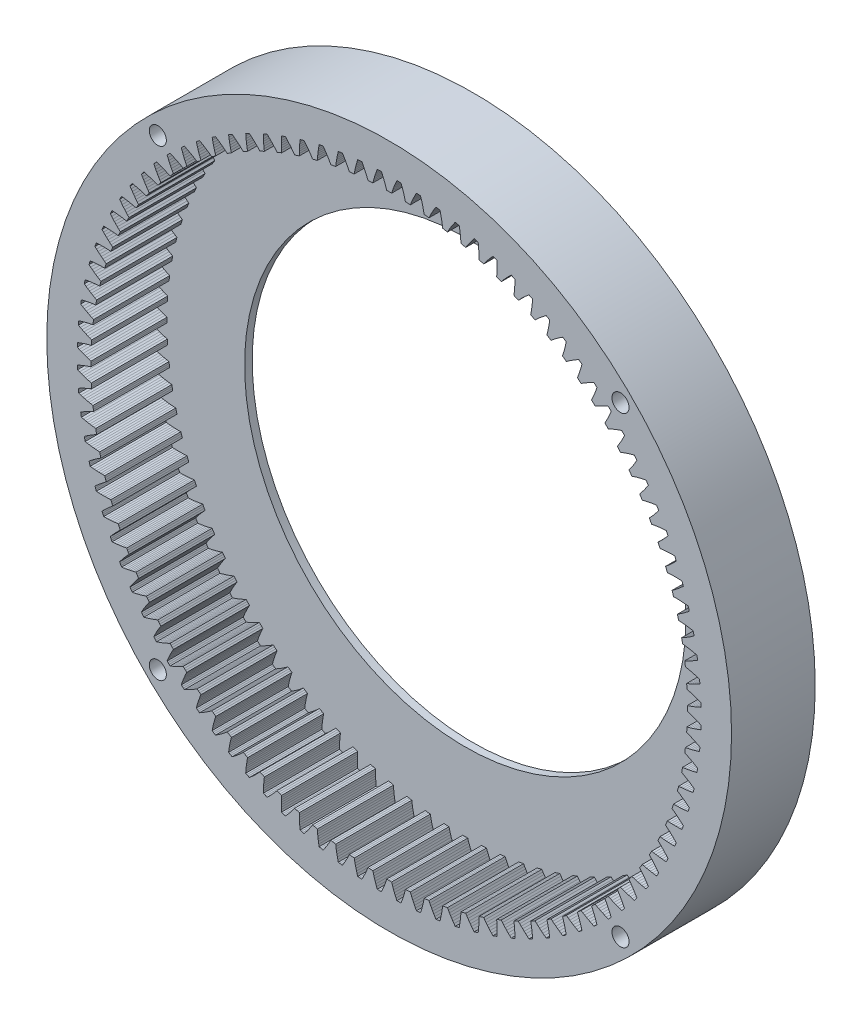
SolidWorks part; units mm, degrees
ref_plane "Спереди" through (0, 0, 0) normal (0, 0, 1) x (1, 0, 0)
ref_plane "Сверху" through (0, 0, 0) normal (0, 1, 0) x (1, 0, 0)
ref_plane "Справа" through (0, 0, 0) normal (1, 0, 0) x (0, 0, -1)
sketch "Эскиз1" plane through (0, 0, 0) normal (0, 0, 1) x (1, 0, 0)
  line L0 (81.9747, -2.0375) -> (81.4657, -1.8058)
  line L1 (81.4657, -1.8058) -> (80.9559, -1.5847)
  line L2 (80.9559, -1.5847) -> (80.4454, -1.3743)
  line L3 (80.4454, -1.3743) -> (79.9342, -1.175)
  line L4 (79.9342, -1.175) -> (79.4224, -0.9873)
  line L5 (79.4224, -0.9873) -> (78.9101, -0.8116)
  line L6 (78.9101, -0.8116) -> (78.3973, -0.6485)
  line L7 (78.3973, -0.6485) -> (78.3997, -0.2162)
  line L8 (78.3997, -0.2162) -> (78.3997, 0.2162)
  line L9 (78.3997, 0.2162) -> (78.3973, 0.6485)
  line L10 (78.3973, 0.6485) -> (78.9101, 0.8116)
  line L11 (78.9101, 0.8116) -> (79.4224, 0.9873)
  line L12 (79.4224, 0.9873) -> (79.9342, 1.175)
  line L13 (79.9342, 1.175) -> (80.4454, 1.3743)
  line L14 (80.4454, 1.3743) -> (80.9559, 1.5847)
  line L15 (80.9559, 1.5847) -> (81.4657, 1.8058)
  line L16 (81.4657, 1.8058) -> (81.9747, 2.0375)
  line L17 (81.9747, 2.0375) -> (81.965, 2.3963)
  line L18 (81.965, 2.3963) -> (81.9537, 2.7551)
  line L19 (81.9537, 2.7551) -> (81.9409, 3.1138)
  line L20 (81.9409, 3.1138) -> (81.4183, 3.313)
  line L21 (81.4183, 3.313) -> (80.8957, 3.5017)
  line L22 (80.8957, 3.5017) -> (80.373, 3.6796)
  line L23 (80.373, 3.6796) -> (79.8503, 3.8464)
  line L24 (79.8503, 3.8464) -> (79.3277, 4.0016)
  line L25 (79.3277, 4.0016) -> (78.8054, 4.1448)
  line L26 (78.8054, 4.1448) -> (78.2833, 4.2754)
  line L27 (78.2833, 4.2754) -> (78.2586, 4.707)
  line L28 (78.2586, 4.707) -> (78.2314, 5.1385)
  line L29 (78.2314, 5.1385) -> (78.2019, 5.5699)
  line L30 (78.2019, 5.5699) -> (78.7034, 5.7648)
  line L31 (78.7034, 5.7648) -> (79.2037, 5.9723)
  line L32 (79.2037, 5.9723) -> (79.7027, 6.1918)
  line L33 (79.7027, 6.1918) -> (80.2004, 6.4228)
  line L34 (80.2004, 6.4228) -> (80.6967, 6.6648)
  line L35 (80.6967, 6.6648) -> (81.1916, 6.9176)
  line L36 (81.1916, 6.9176) -> (81.685, 7.1807)
  line L37 (81.685, 7.1807) -> (81.6528, 7.5382)
  line L38 (81.6528, 7.5382) -> (81.619, 7.8955)
  line L39 (81.619, 7.8955) -> (81.5837, 8.2528)
  line L40 (81.5837, 8.2528) -> (81.0497, 8.4188)
  line L41 (81.0497, 8.4188) -> (80.5162, 8.5743)
  line L42 (80.5162, 8.5743) -> (79.9833, 8.719)
  line L43 (79.9833, 8.719) -> (79.4512, 8.8527)
  line L44 (79.4512, 8.8527) -> (78.9199, 8.9748)
  line L45 (78.9199, 8.9748) -> (78.3896, 9.0849)
  line L46 (78.3896, 9.0849) -> (77.8604, 9.1824)
  line L47 (77.8604, 9.1824) -> (77.8086, 9.6116)
  line L48 (77.8086, 9.6116) -> (77.7544, 10.0406)
  line L49 (77.7544, 10.0406) -> (77.6978, 10.4692)
  line L50 (77.6978, 10.4692) -> (78.1862, 10.6952)
  line L51 (78.1862, 10.6952) -> (78.6724, 10.9338)
  line L52 (78.6724, 10.9338) -> (79.1566, 11.1842)
  line L53 (79.1566, 11.1842) -> (79.6388, 11.4459)
  line L54 (79.6388, 11.4459) -> (80.1189, 11.7186)
  line L55 (80.1189, 11.7186) -> (80.597, 12.002)
  line L56 (80.597, 12.002) -> (81.0729, 12.2956)
  line L57 (81.0729, 12.2956) -> (81.0183, 12.6503)
  line L58 (81.0183, 12.6503) -> (80.9622, 13.0049)
  line L59 (80.9622, 13.0049) -> (80.9045, 13.3591)
  line L60 (80.9045, 13.3591) -> (80.3611, 13.4913)
  line L61 (80.3611, 13.4913) -> (79.8189, 13.613)
  line L62 (79.8189, 13.613) -> (79.278, 13.724)
  line L63 (79.278, 13.724) -> (78.7385, 13.824)
  line L64 (78.7385, 13.824) -> (78.2006, 13.9125)
  line L65 (78.2006, 13.9125) -> (77.6645, 13.9891)
  line L66 (77.6645, 13.9891) -> (77.1302, 14.0531)
  line L67 (77.1302, 14.0531) -> (77.0515, 14.4783)
  line L68 (77.0515, 14.4783) -> (76.9705, 14.903)
  line L69 (76.9705, 14.903) -> (76.8872, 15.3272)
  line L70 (76.8872, 15.3272) -> (77.3603, 15.5835)
  line L71 (77.3603, 15.5835) -> (77.8306, 15.8521)
  line L72 (77.8306, 15.8521) -> (78.2982, 16.1324)
  line L73 (78.2982, 16.1324) -> (78.763, 16.4239)
  line L74 (78.763, 16.4239) -> (79.225, 16.7262)
  line L75 (79.225, 16.7262) -> (79.6843, 17.039)
  line L76 (79.6843, 17.039) -> (80.1409, 17.3619)
  line L77 (80.1409, 17.3619) -> (80.0641, 17.7125)
  line L78 (80.0641, 17.7125) -> (79.9858, 18.0629)
  line L79 (79.9858, 18.0629) -> (79.906, 18.4128)
  line L80 (79.906, 18.4128) -> (79.3554, 18.5106)
  line L81 (79.3554, 18.5106) -> (78.8066, 18.598)
  line L82 (78.8066, 18.598) -> (78.2598, 18.6749)
  line L83 (78.2598, 18.6749) -> (77.7152, 18.7407)
  line L84 (77.7152, 18.7407) -> (77.1728, 18.7953)
  line L85 (77.1728, 18.7953) -> (76.6328, 18.8381)
  line L86 (76.6328, 18.8381) -> (76.0956, 18.8685)
  line L87 (76.0956, 18.8685) -> (75.9904, 19.2878)
  line L88 (75.9904, 19.2878) -> (75.8829, 19.7066)
  line L89 (75.8829, 19.7066) -> (75.773, 20.1248)
  line L90 (75.773, 20.1248) -> (76.2292, 20.4102)
  line L91 (76.2292, 20.4102) -> (76.6817, 20.7078)
  line L92 (76.6817, 20.7078) -> (77.1307, 21.0169)
  line L93 (77.1307, 21.0169) -> (77.5763, 21.3371)
  line L94 (77.5763, 21.3371) -> (78.0184, 21.6678)
  line L95 (78.0184, 21.6678) -> (78.4572, 22.0088)
  line L96 (78.4572, 22.0088) -> (78.8926, 22.3597)
  line L97 (78.8926, 22.3597) -> (78.794, 22.7049)
  line L98 (78.794, 22.7049) -> (78.6938, 23.0496)
  line L99 (78.6938, 23.0496) -> (78.5922, 23.3938)
  line L100 (78.5922, 23.3938) -> (78.0365, 23.4568)
  line L101 (78.0365, 23.4568) -> (77.4833, 23.5096)
  line L102 (77.4833, 23.5096) -> (76.9328, 23.552)
  line L103 (76.9328, 23.552) -> (76.3851, 23.5835)
  line L104 (76.3851, 23.5835) -> (75.8403, 23.6039)
  line L105 (75.8403, 23.6039) -> (75.2988, 23.6127)
  line L106 (75.2988, 23.6127) -> (74.7607, 23.6093)
  line L107 (74.7607, 23.6093) -> (74.6294, 24.0212)
  line L108 (74.6294, 24.0212) -> (74.4957, 24.4324)
  line L109 (74.4957, 24.4324) -> (74.3599, 24.8429)
  line L110 (74.3599, 24.8429) -> (74.7972, 25.1564)
  line L111 (74.7972, 25.1564) -> (75.2301, 25.4818)
  line L112 (75.2301, 25.4818) -> (75.6589, 25.8185)
  line L113 (75.6589, 25.8185) -> (76.0834, 26.166)
  line L114 (76.0834, 26.166) -> (76.504, 26.5239)
  line L115 (76.504, 26.5239) -> (76.9205, 26.8917)
  line L116 (76.9205, 26.8917) -> (77.3329, 27.2693)
  line L117 (77.3329, 27.2693) -> (77.2128, 27.6076)
  line L118 (77.2128, 27.6076) -> (77.0912, 27.9453)
  line L119 (77.0912, 27.9453) -> (76.9682, 28.2825)
  line L120 (76.9682, 28.2825) -> (76.4097, 28.3105)
  line L121 (76.4097, 28.3105) -> (75.8543, 28.3285)
  line L122 (75.8543, 28.3285) -> (75.3022, 28.3362)
  line L123 (75.3022, 28.3362) -> (74.7535, 28.3333)
  line L124 (74.7535, 28.3333) -> (74.2086, 28.3194)
  line L125 (74.2086, 28.3194) -> (73.6675, 28.2942)
  line L126 (73.6675, 28.2942) -> (73.1307, 28.257)
  line L127 (73.1307, 28.257) -> (72.9738, 28.6599)
  line L128 (72.9738, 28.6599) -> (72.8146, 29.0619)
  line L129 (72.8146, 29.0619) -> (72.6532, 29.463)
  line L130 (72.6532, 29.463) -> (73.07, 29.8033)
  line L131 (73.07, 29.8033) -> (73.4817, 30.1553)
  line L132 (73.4817, 30.1553) -> (73.8884, 30.5182)
  line L133 (73.8884, 30.5182) -> (74.2903, 30.8917)
  line L134 (74.2903, 30.8917) -> (74.6876, 31.2753)
  line L135 (74.6876, 31.2753) -> (75.0801, 31.6686)
  line L136 (75.0801, 31.6686) -> (75.4681, 32.0713)
  line L137 (75.4681, 32.0713) -> (75.327, 32.4013)
  line L138 (75.327, 32.4013) -> (75.1844, 32.7308)
  line L139 (75.1844, 32.7308) -> (75.0404, 33.0596)
  line L140 (75.0404, 33.0596) -> (74.4813, 33.0524)
  line L141 (74.4813, 33.0524) -> (73.9258, 33.0355)
  line L142 (73.9258, 33.0355) -> (73.3743, 33.0085)
  line L143 (73.3743, 33.0085) -> (72.8269, 32.9712)
  line L144 (72.8269, 32.9712) -> (72.2839, 32.9231)
  line L145 (72.2839, 32.9231) -> (71.7456, 32.8639)
  line L146 (71.7456, 32.8639) -> (71.2121, 32.7931)
  line L147 (71.2121, 32.7931) -> (71.0302, 33.1854)
  line L148 (71.0302, 33.1854) -> (70.8461, 33.5766)
  line L149 (70.8461, 33.5766) -> (70.6599, 33.9668)
  line L150 (70.6599, 33.9668) -> (71.0544, 34.3326)
  line L151 (71.0544, 34.3326) -> (71.4432, 34.7097)
  line L152 (71.4432, 34.7097) -> (71.8263, 35.0975)
  line L153 (71.8263, 35.0975) -> (72.204, 35.4955)
  line L154 (72.204, 35.4955) -> (72.5764, 35.9032)
  line L155 (72.5764, 35.9032) -> (72.9435, 36.3204)
  line L156 (72.9435, 36.3204) -> (73.3054, 36.7467)
  line L157 (73.3054, 36.7467) -> (73.1438, 37.0672)
  line L158 (73.1438, 37.0672) -> (72.9809, 37.387)
  line L159 (72.9809, 37.387) -> (72.8165, 37.7062)
  line L160 (72.8165, 37.7062) -> (72.2589, 37.6639)
  line L161 (72.2589, 37.6639) -> (71.7056, 37.6121)
  line L162 (71.7056, 37.6121) -> (71.1569, 37.5506)
  line L163 (71.1569, 37.5506) -> (70.613, 37.4789)
  line L164 (70.613, 37.4789) -> (70.074, 37.3969)
  line L165 (70.074, 37.3969) -> (69.5404, 37.304)
  line L166 (69.5404, 37.304) -> (69.0125, 37.1999)
  line L167 (69.0125, 37.1999) -> (68.8063, 37.5799)
  line L168 (68.8063, 37.5799) -> (68.598, 37.9588)
  line L169 (68.598, 37.9588) -> (68.3877, 38.3365)
  line L170 (68.3877, 38.3365) -> (68.7585, 38.7264)
  line L171 (68.7585, 38.7264) -> (69.1228, 39.1272)
  line L172 (69.1228, 39.1272) -> (69.4808, 39.5383)
  line L173 (69.4808, 39.5383) -> (69.8328, 39.9592)
  line L174 (69.8328, 39.9592) -> (70.1788, 40.3895)
  line L175 (70.1788, 40.3895) -> (70.519, 40.8289)
  line L176 (70.519, 40.8289) -> (70.8534, 41.2771)
  line L177 (70.8534, 41.2771) -> (70.672, 41.5868)
  line L178 (70.672, 41.5868) -> (70.4893, 41.8958)
  line L179 (70.4893, 41.8958) -> (70.3052, 42.2039)
  line L180 (70.3052, 42.2039) -> (69.7514, 42.1268)
  line L181 (69.7514, 42.1268) -> (69.2025, 42.0404)
  line L182 (69.2025, 42.0404) -> (68.6587, 41.9445)
  line L183 (68.6587, 41.9445) -> (68.1203, 41.8388)
  line L184 (68.1203, 41.8388) -> (67.5876, 41.7231)
  line L185 (67.5876, 41.7231) -> (67.0609, 41.5969)
  line L186 (67.0609, 41.5969) -> (66.5405, 41.4598)
  line L187 (66.5405, 41.4598) -> (66.3109, 41.8261)
  line L188 (66.3109, 41.8261) -> (66.0792, 42.1912)
  line L189 (66.0792, 42.1912) -> (65.8455, 42.555)
  line L190 (65.8455, 42.555) -> (66.1911, 42.9674)
  line L191 (66.1911, 42.9674) -> (66.5296, 43.3903)
  line L192 (66.5296, 43.3903) -> (66.8611, 43.823)
  line L193 (66.8611, 43.823) -> (67.1859, 44.2652)
  line L194 (67.1859, 44.2652) -> (67.5042, 44.7163)
  line L195 (67.5042, 44.7163) -> (67.8161, 45.1762)
  line L196 (67.8161, 45.1762) -> (68.1218, 45.6445)
  line L197 (68.1218, 45.6445) -> (67.9213, 45.9423)
  line L198 (67.9213, 45.9423) -> (67.7196, 46.2392)
  line L199 (67.7196, 46.2392) -> (67.5165, 46.5352)
  line L200 (67.5165, 46.5352) -> (66.9686, 46.4234)
  line L201 (66.9686, 46.4234) -> (66.4262, 46.3027)
  line L202 (66.4262, 46.3027) -> (65.8895, 46.1728)
  line L203 (65.8895, 46.1728) -> (65.3588, 46.0336)
  line L204 (65.3588, 46.0336) -> (64.8344, 45.8846)
  line L205 (64.8344, 45.8846) -> (64.3167, 45.7256)
  line L206 (64.3167, 45.7256) -> (63.806, 45.5561)
  line L207 (63.806, 45.5561) -> (63.5538, 45.9073)
  line L208 (63.5538, 45.9073) -> (63.2996, 46.2571)
  line L209 (63.2996, 46.2571) -> (63.0436, 46.6055)
  line L210 (63.0436, 46.6055) -> (63.3626, 47.0388)
  line L211 (63.3626, 47.0388) -> (63.6738, 47.4821)
  line L212 (63.6738, 47.4821) -> (63.9775, 47.9348)
  line L213 (63.9775, 47.9348) -> (64.2739, 48.3964)
  line L214 (64.2739, 48.3964) -> (64.5633, 48.8667)
  line L215 (64.5633, 48.8667) -> (64.8457, 49.3453)
  line L216 (64.8457, 49.3453) -> (65.1213, 49.8319)
  line L217 (65.1213, 49.8319) -> (64.9026, 50.1164)
  line L218 (64.9026, 50.1164) -> (64.6826, 50.4001)
  line L219 (64.6826, 50.4001) -> (64.4613, 50.6827)
  line L220 (64.4613, 50.6827) -> (63.9215, 50.5368)
  line L221 (63.9215, 50.5368) -> (63.3877, 50.3822)
  line L222 (63.3877, 50.3822) -> (62.8603, 50.2189)
  line L223 (62.8603, 50.2189) -> (62.3394, 50.0466)
  line L224 (62.3394, 50.0466) -> (61.8254, 49.8651)
  line L225 (61.8254, 49.8651) -> (61.3186, 49.6739)
  line L226 (61.3186, 49.6739) -> (60.8196, 49.4726)
  line L227 (60.8196, 49.4726) -> (60.5458, 49.8073)
  line L228 (60.5458, 49.8073) -> (60.2702, 50.1404)
  line L229 (60.2702, 50.1404) -> (59.9928, 50.472)
  line L230 (59.9928, 50.472) -> (60.284, 50.9245)
  line L231 (60.284, 50.9245) -> (60.5667, 51.3865)
  line L232 (60.5667, 51.3865) -> (60.8414, 51.8574)
  line L233 (60.8414, 51.8574) -> (61.1082, 52.3367)
  line L234 (61.1082, 52.3367) -> (61.3675, 52.8243)
  line L235 (61.3675, 52.8243) -> (61.6193, 53.3196)
  line L236 (61.6193, 53.3196) -> (61.8638, 53.8225)
  line L237 (61.8638, 53.8225) -> (61.6277, 54.0928)
  line L238 (61.6277, 54.0928) -> (61.3903, 54.3621)
  line L239 (61.3903, 54.3621) -> (61.1517, 54.6303)
  line L240 (61.1517, 54.6303) -> (60.6221, 54.4507)
  line L241 (60.6221, 54.4507) -> (60.0991, 54.263)
  line L242 (60.0991, 54.263) -> (59.5829, 54.0669)
  line L243 (59.5829, 54.0669) -> (59.0739, 53.8622)
  line L244 (59.0739, 53.8622) -> (58.5723, 53.6487)
  line L245 (58.5723, 53.6487) -> (58.0786, 53.4261)
  line L246 (58.0786, 53.4261) -> (57.5931, 53.1939)
  line L247 (57.5931, 53.1939) -> (57.2989, 53.5107)
  line L248 (57.2989, 53.5107) -> (57.0029, 53.8259)
  line L249 (57.0029, 53.8259) -> (56.7052, 54.1394)
  line L250 (56.7052, 54.1394) -> (56.9674, 54.6093)
  line L251 (56.9674, 54.6093) -> (57.2206, 55.0881)
  line L252 (57.2206, 55.0881) -> (57.4652, 55.5753)
  line L253 (57.4652, 55.5753) -> (57.7014, 56.0705)
  line L254 (57.7014, 56.0705) -> (57.9295, 56.5733)
  line L255 (57.9295, 56.5733) -> (58.1498, 57.0835)
  line L256 (58.1498, 57.0835) -> (58.3622, 57.6008)
  line L257 (58.3622, 57.6008) -> (58.1095, 57.8557)
  line L258 (58.1095, 57.8557) -> (57.8557, 58.1095)
  line L259 (57.8557, 58.1095) -> (57.6008, 58.3622)
  line L260 (57.6008, 58.3622) -> (57.0835, 58.1498)
  line L261 (57.0835, 58.1498) -> (56.5733, 57.9295)
  line L262 (56.5733, 57.9295) -> (56.0705, 57.7014)
  line L263 (56.0705, 57.7014) -> (55.5753, 57.4652)
  line L264 (55.5753, 57.4652) -> (55.0881, 57.2206)
  line L265 (55.0881, 57.2206) -> (54.6093, 56.9674)
  line L266 (54.6093, 56.9674) -> (54.1394, 56.7052)
  line L267 (54.1394, 56.7052) -> (53.8259, 57.0029)
  line L268 (53.8259, 57.0029) -> (53.5107, 57.2989)
  line L269 (53.5107, 57.2989) -> (53.1939, 57.5931)
  line L270 (53.1939, 57.5931) -> (53.4261, 58.0786)
  line L271 (53.4261, 58.0786) -> (53.6487, 58.5723)
  line L272 (53.6487, 58.5723) -> (53.8622, 59.0739)
  line L273 (53.8622, 59.0739) -> (54.0669, 59.5829)
  line L274 (54.0669, 59.5829) -> (54.263, 60.0991)
  line L275 (54.263, 60.0991) -> (54.4507, 60.6221)
  line L276 (54.4507, 60.6221) -> (54.6303, 61.1517)
  line L277 (54.6303, 61.1517) -> (54.3621, 61.3903)
  line L278 (54.3621, 61.3903) -> (54.0928, 61.6277)
  line L279 (54.0928, 61.6277) -> (53.8225, 61.8638)
  line L280 (53.8225, 61.8638) -> (53.3196, 61.6193)
  line L281 (53.3196, 61.6193) -> (52.8243, 61.3675)
  line L282 (52.8243, 61.3675) -> (52.3367, 61.1082)
  line L283 (52.3367, 61.1082) -> (51.8574, 60.8414)
  line L284 (51.8574, 60.8414) -> (51.3865, 60.5667)
  line L285 (51.3865, 60.5667) -> (50.9245, 60.284)
  line L286 (50.9245, 60.284) -> (50.472, 59.9928)
  line L287 (50.472, 59.9928) -> (50.1404, 60.2702)
  line L288 (50.1404, 60.2702) -> (49.8073, 60.5458)
  line L289 (49.8073, 60.5458) -> (49.4726, 60.8196)
  line L290 (49.4726, 60.8196) -> (49.6739, 61.3186)
  line L291 (49.6739, 61.3186) -> (49.8651, 61.8254)
  line L292 (49.8651, 61.8254) -> (50.0466, 62.3394)
  line L293 (50.0466, 62.3394) -> (50.2189, 62.8603)
  line L294 (50.2189, 62.8603) -> (50.3822, 63.3877)
  line L295 (50.3822, 63.3877) -> (50.5368, 63.9215)
  line L296 (50.5368, 63.9215) -> (50.6827, 64.4613)
  line L297 (50.6827, 64.4613) -> (50.4001, 64.6826)
  line L298 (50.4001, 64.6826) -> (50.1164, 64.9026)
  line L299 (50.1164, 64.9026) -> (49.8319, 65.1213)
  line L300 (49.8319, 65.1213) -> (49.3453, 64.8457)
  line L301 (49.3453, 64.8457) -> (48.8667, 64.5633)
  line L302 (48.8667, 64.5633) -> (48.3964, 64.2739)
  line L303 (48.3964, 64.2739) -> (47.9348, 63.9775)
  line L304 (47.9348, 63.9775) -> (47.4821, 63.6738)
  line L305 (47.4821, 63.6738) -> (47.0388, 63.3626)
  line L306 (47.0388, 63.3626) -> (46.6055, 63.0436)
  line L307 (46.6055, 63.0436) -> (46.2571, 63.2996)
  line L308 (46.2571, 63.2996) -> (45.9073, 63.5538)
  line L309 (45.9073, 63.5538) -> (45.5561, 63.806)
  line L310 (45.5561, 63.806) -> (45.7256, 64.3167)
  line L311 (45.7256, 64.3167) -> (45.8846, 64.8344)
  line L312 (45.8846, 64.8344) -> (46.0336, 65.3588)
  line L313 (46.0336, 65.3588) -> (46.1728, 65.8895)
  line L314 (46.1728, 65.8895) -> (46.3027, 66.4262)
  line L315 (46.3027, 66.4262) -> (46.4234, 66.9686)
  line L316 (46.4234, 66.9686) -> (46.5352, 67.5165)
  line L317 (46.5352, 67.5165) -> (46.2392, 67.7196)
  line L318 (46.2392, 67.7196) -> (45.9423, 67.9213)
  line L319 (45.9423, 67.9213) -> (45.6445, 68.1218)
  line L320 (45.6445, 68.1218) -> (45.1762, 67.8161)
  line L321 (45.1762, 67.8161) -> (44.7163, 67.5042)
  line L322 (44.7163, 67.5042) -> (44.2652, 67.1859)
  line L323 (44.2652, 67.1859) -> (43.823, 66.8611)
  line L324 (43.823, 66.8611) -> (43.3903, 66.5296)
  line L325 (43.3903, 66.5296) -> (42.9674, 66.1911)
  line L326 (42.9674, 66.1911) -> (42.555, 65.8455)
  line L327 (42.555, 65.8455) -> (42.1912, 66.0792)
  line L328 (42.1912, 66.0792) -> (41.8261, 66.3109)
  line L329 (41.8261, 66.3109) -> (41.4598, 66.5405)
  line L330 (41.4598, 66.5405) -> (41.5969, 67.0609)
  line L331 (41.5969, 67.0609) -> (41.7231, 67.5876)
  line L332 (41.7231, 67.5876) -> (41.8388, 68.1203)
  line L333 (41.8388, 68.1203) -> (41.9445, 68.6587)
  line L334 (41.9445, 68.6587) -> (42.0404, 69.2025)
  line L335 (42.0404, 69.2025) -> (42.1268, 69.7514)
  line L336 (42.1268, 69.7514) -> (42.2039, 70.3052)
  line L337 (42.2039, 70.3052) -> (41.8958, 70.4893)
  line L338 (41.8958, 70.4893) -> (41.5868, 70.672)
  line L339 (41.5868, 70.672) -> (41.2771, 70.8534)
  line L340 (41.2771, 70.8534) -> (40.8289, 70.519)
  line L341 (40.8289, 70.519) -> (40.3895, 70.1788)
  line L342 (40.3895, 70.1788) -> (39.9592, 69.8328)
  line L343 (39.9592, 69.8328) -> (39.5383, 69.4808)
  line L344 (39.5383, 69.4808) -> (39.1272, 69.1228)
  line L345 (39.1272, 69.1228) -> (38.7264, 68.7585)
  line L346 (38.7264, 68.7585) -> (38.3365, 68.3877)
  line L347 (38.3365, 68.3877) -> (37.9588, 68.598)
  line L348 (37.9588, 68.598) -> (37.5799, 68.8063)
  line L349 (37.5799, 68.8063) -> (37.1999, 69.0125)
  line L350 (37.1999, 69.0125) -> (37.304, 69.5404)
  line L351 (37.304, 69.5404) -> (37.3969, 70.074)
  line L352 (37.3969, 70.074) -> (37.4789, 70.613)
  line L353 (37.4789, 70.613) -> (37.5506, 71.1569)
  line L354 (37.5506, 71.1569) -> (37.6121, 71.7056)
  line L355 (37.6121, 71.7056) -> (37.6639, 72.2589)
  line L356 (37.6639, 72.2589) -> (37.7062, 72.8165)
  line L357 (37.7062, 72.8165) -> (37.387, 72.9809)
  line L358 (37.387, 72.9809) -> (37.0672, 73.1438)
  line L359 (37.0672, 73.1438) -> (36.7467, 73.3054)
  line L360 (36.7467, 73.3054) -> (36.3204, 72.9435)
  line L361 (36.3204, 72.9435) -> (35.9032, 72.5764)
  line L362 (35.9032, 72.5764) -> (35.4955, 72.204)
  line L363 (35.4955, 72.204) -> (35.0975, 71.8263)
  line L364 (35.0975, 71.8263) -> (34.7097, 71.4432)
  line L365 (34.7097, 71.4432) -> (34.3326, 71.0544)
  line L366 (34.3326, 71.0544) -> (33.9668, 70.6599)
  line L367 (33.9668, 70.6599) -> (33.5766, 70.8461)
  line L368 (33.5766, 70.8461) -> (33.1854, 71.0302)
  line L369 (33.1854, 71.0302) -> (32.7931, 71.2121)
  line L370 (32.7931, 71.2121) -> (32.8639, 71.7456)
  line L371 (32.8639, 71.7456) -> (32.9231, 72.2839)
  line L372 (32.9231, 72.2839) -> (32.9712, 72.8269)
  line L373 (32.9712, 72.8269) -> (33.0085, 73.3743)
  line L374 (33.0085, 73.3743) -> (33.0355, 73.9258)
  line L375 (33.0355, 73.9258) -> (33.0524, 74.4813)
  line L376 (33.0524, 74.4813) -> (33.0596, 75.0404)
  line L377 (33.0596, 75.0404) -> (32.7308, 75.1844)
  line L378 (32.7308, 75.1844) -> (32.4013, 75.327)
  line L379 (32.4013, 75.327) -> (32.0713, 75.4681)
  line L380 (32.0713, 75.4681) -> (31.6686, 75.0801)
  line L381 (31.6686, 75.0801) -> (31.2753, 74.6876)
  line L382 (31.2753, 74.6876) -> (30.8917, 74.2903)
  line L383 (30.8917, 74.2903) -> (30.5182, 73.8884)
  line L384 (30.5182, 73.8884) -> (30.1553, 73.4817)
  line L385 (30.1553, 73.4817) -> (29.8033, 73.07)
  line L386 (29.8033, 73.07) -> (29.463, 72.6532)
  line L387 (29.463, 72.6532) -> (29.0619, 72.8146)
  line L388 (29.0619, 72.8146) -> (28.6599, 72.9738)
  line L389 (28.6599, 72.9738) -> (28.257, 73.1307)
  line L390 (28.257, 73.1307) -> (28.2942, 73.6675)
  line L391 (28.2942, 73.6675) -> (28.3194, 74.2086)
  line L392 (28.3194, 74.2086) -> (28.3333, 74.7535)
  line L393 (28.3333, 74.7535) -> (28.3362, 75.3022)
  line L394 (28.3362, 75.3022) -> (28.3285, 75.8543)
  line L395 (28.3285, 75.8543) -> (28.3105, 76.4097)
  line L396 (28.3105, 76.4097) -> (28.2825, 76.9682)
  line L397 (28.2825, 76.9682) -> (27.9453, 77.0912)
  line L398 (27.9453, 77.0912) -> (27.6076, 77.2128)
  line L399 (27.6076, 77.2128) -> (27.2693, 77.3329)
  line L400 (27.2693, 77.3329) -> (26.8917, 76.9205)
  line L401 (26.8917, 76.9205) -> (26.5239, 76.504)
  line L402 (26.5239, 76.504) -> (26.166, 76.0834)
  line L403 (26.166, 76.0834) -> (25.8185, 75.6589)
  line L404 (25.8185, 75.6589) -> (25.4818, 75.2301)
  line L405 (25.4818, 75.2301) -> (25.1564, 74.7972)
  line L406 (25.1564, 74.7972) -> (24.8429, 74.3599)
  line L407 (24.8429, 74.3599) -> (24.4324, 74.4957)
  line L408 (24.4324, 74.4957) -> (24.0212, 74.6294)
  line L409 (24.0212, 74.6294) -> (23.6093, 74.7607)
  line L410 (23.6093, 74.7607) -> (23.6127, 75.2988)
  line L411 (23.6127, 75.2988) -> (23.6039, 75.8403)
  line L412 (23.6039, 75.8403) -> (23.5835, 76.3851)
  line L413 (23.5835, 76.3851) -> (23.552, 76.9328)
  line L414 (23.552, 76.9328) -> (23.5096, 77.4833)
  line L415 (23.5096, 77.4833) -> (23.4568, 78.0365)
  line L416 (23.4568, 78.0365) -> (23.3938, 78.5922)
  line L417 (23.3938, 78.5922) -> (23.0496, 78.6938)
  line L418 (23.0496, 78.6938) -> (22.7049, 78.794)
  line L419 (22.7049, 78.794) -> (22.3597, 78.8926)
  line L420 (22.3597, 78.8926) -> (22.0088, 78.4572)
  line L421 (22.0088, 78.4572) -> (21.6678, 78.0184)
  line L422 (21.6678, 78.0184) -> (21.3371, 77.5763)
  line L423 (21.3371, 77.5763) -> (21.0169, 77.1307)
  line L424 (21.0169, 77.1307) -> (20.7078, 76.6817)
  line L425 (20.7078, 76.6817) -> (20.4102, 76.2292)
  line L426 (20.4102, 76.2292) -> (20.1248, 75.773)
  line L427 (20.1248, 75.773) -> (19.7066, 75.8829)
  line L428 (19.7066, 75.8829) -> (19.2878, 75.9904)
  line L429 (19.2878, 75.9904) -> (18.8685, 76.0956)
  line L430 (18.8685, 76.0956) -> (18.8381, 76.6328)
  line L431 (18.8381, 76.6328) -> (18.7953, 77.1728)
  line L432 (18.7953, 77.1728) -> (18.7407, 77.7152)
  line L433 (18.7407, 77.7152) -> (18.6749, 78.2598)
  line L434 (18.6749, 78.2598) -> (18.598, 78.8066)
  line L435 (18.598, 78.8066) -> (18.5106, 79.3554)
  line L436 (18.5106, 79.3554) -> (18.4128, 79.906)
  line L437 (18.4128, 79.906) -> (18.0629, 79.9858)
  line L438 (18.0629, 79.9858) -> (17.7125, 80.0641)
  line L439 (17.7125, 80.0641) -> (17.3619, 80.1409)
  line L440 (17.3619, 80.1409) -> (17.039, 79.6843)
  line L441 (17.039, 79.6843) -> (16.7262, 79.225)
  line L442 (16.7262, 79.225) -> (16.4239, 78.763)
  line L443 (16.4239, 78.763) -> (16.1324, 78.2982)
  line L444 (16.1324, 78.2982) -> (15.8521, 77.8306)
  line L445 (15.8521, 77.8306) -> (15.5835, 77.3603)
  line L446 (15.5835, 77.3603) -> (15.3272, 76.8872)
  line L447 (15.3272, 76.8872) -> (14.903, 76.9705)
  line L448 (14.903, 76.9705) -> (14.4783, 77.0515)
  line L449 (14.4783, 77.0515) -> (14.0531, 77.1302)
  line L450 (14.0531, 77.1302) -> (13.9891, 77.6645)
  line L451 (13.9891, 77.6645) -> (13.9125, 78.2006)
  line L452 (13.9125, 78.2006) -> (13.824, 78.7385)
  line L453 (13.824, 78.7385) -> (13.724, 79.278)
  line L454 (13.724, 79.278) -> (13.613, 79.8189)
  line L455 (13.613, 79.8189) -> (13.4913, 80.3611)
  line L456 (13.4913, 80.3611) -> (13.3591, 80.9045)
  line L457 (13.3591, 80.9045) -> (13.0049, 80.9622)
  line L458 (13.0049, 80.9622) -> (12.6503, 81.0183)
  line L459 (12.6503, 81.0183) -> (12.2956, 81.0729)
  line L460 (12.2956, 81.0729) -> (12.002, 80.597)
  line L461 (12.002, 80.597) -> (11.7186, 80.1189)
  line L462 (11.7186, 80.1189) -> (11.4459, 79.6388)
  line L463 (11.4459, 79.6388) -> (11.1842, 79.1566)
  line L464 (11.1842, 79.1566) -> (10.9338, 78.6724)
  line L465 (10.9338, 78.6724) -> (10.6952, 78.1862)
  line L466 (10.6952, 78.1862) -> (10.4692, 77.6978)
  line L467 (10.4692, 77.6978) -> (10.0406, 77.7544)
  line L468 (10.0406, 77.7544) -> (9.6116, 77.8086)
  line L469 (9.6116, 77.8086) -> (9.1824, 77.8604)
  line L470 (9.1824, 77.8604) -> (9.0849, 78.3896)
  line L471 (9.0849, 78.3896) -> (8.9748, 78.9199)
  line L472 (8.9748, 78.9199) -> (8.8527, 79.4512)
  line L473 (8.8527, 79.4512) -> (8.719, 79.9833)
  line L474 (8.719, 79.9833) -> (8.5743, 80.5162)
  line L475 (8.5743, 80.5162) -> (8.4188, 81.0497)
  line L476 (8.4188, 81.0497) -> (8.2528, 81.5837)
  line L477 (8.2528, 81.5837) -> (7.8955, 81.619)
  line L478 (7.8955, 81.619) -> (7.5382, 81.6528)
  line L479 (7.5382, 81.6528) -> (7.1807, 81.685)
  line L480 (7.1807, 81.685) -> (6.9176, 81.1916)
  line L481 (6.9176, 81.1916) -> (6.6648, 80.6967)
  line L482 (6.6648, 80.6967) -> (6.4228, 80.2004)
  line L483 (6.4228, 80.2004) -> (6.1918, 79.7027)
  line L484 (6.1918, 79.7027) -> (5.9723, 79.2037)
  line L485 (5.9723, 79.2037) -> (5.7648, 78.7034)
  line L486 (5.7648, 78.7034) -> (5.5699, 78.2019)
  line L487 (5.5699, 78.2019) -> (5.1385, 78.2314)
  line L488 (5.1385, 78.2314) -> (4.707, 78.2586)
  line L489 (4.707, 78.2586) -> (4.2754, 78.2833)
  line L490 (4.2754, 78.2833) -> (4.1448, 78.8054)
  line L491 (4.1448, 78.8054) -> (4.0016, 79.3277)
  line L492 (4.0016, 79.3277) -> (3.8464, 79.8503)
  line L493 (3.8464, 79.8503) -> (3.6796, 80.373)
  line L494 (3.6796, 80.373) -> (3.5017, 80.8957)
  line L495 (3.5017, 80.8957) -> (3.313, 81.4183)
  line L496 (3.313, 81.4183) -> (3.1138, 81.9409)
  line L497 (3.1138, 81.9409) -> (2.7551, 81.9537)
  line L498 (2.7551, 81.9537) -> (2.3963, 81.965)
  line L499 (2.3963, 81.965) -> (2.0375, 81.9747)
  line L500 (2.0375, 81.9747) -> (1.8058, 81.4657)
  line L501 (1.8058, 81.4657) -> (1.5847, 80.9559)
  line L502 (1.5847, 80.9559) -> (1.3743, 80.4454)
  line L503 (1.3743, 80.4454) -> (1.175, 79.9342)
  line L504 (1.175, 79.9342) -> (0.9873, 79.4224)
  line L505 (0.9873, 79.4224) -> (0.8116, 78.9101)
  line L506 (0.8116, 78.9101) -> (0.6485, 78.3973)
  line L507 (0.6485, 78.3973) -> (0.2162, 78.3997)
  line L508 (0.2162, 78.3997) -> (-0.2162, 78.3997)
  line L509 (-0.2162, 78.3997) -> (-0.6485, 78.3973)
  line L510 (-0.6485, 78.3973) -> (-0.8116, 78.9101)
  line L511 (-0.8116, 78.9101) -> (-0.9873, 79.4224)
  line L512 (-0.9873, 79.4224) -> (-1.175, 79.9342)
  line L513 (-1.175, 79.9342) -> (-1.3743, 80.4454)
  line L514 (-1.3743, 80.4454) -> (-1.5847, 80.9559)
  line L515 (-1.5847, 80.9559) -> (-1.8058, 81.4657)
  line L516 (-1.8058, 81.4657) -> (-2.0375, 81.9747)
  line L517 (-2.0375, 81.9747) -> (-2.3963, 81.965)
  line L518 (-2.3963, 81.965) -> (-2.7551, 81.9537)
  line L519 (-2.7551, 81.9537) -> (-3.1138, 81.9409)
  line L520 (-3.1138, 81.9409) -> (-3.313, 81.4183)
  line L521 (-3.313, 81.4183) -> (-3.5017, 80.8957)
  line L522 (-3.5017, 80.8957) -> (-3.6796, 80.373)
  line L523 (-3.6796, 80.373) -> (-3.8464, 79.8503)
  line L524 (-3.8464, 79.8503) -> (-4.0016, 79.3277)
  line L525 (-4.0016, 79.3277) -> (-4.1448, 78.8054)
  line L526 (-4.1448, 78.8054) -> (-4.2754, 78.2833)
  line L527 (-4.2754, 78.2833) -> (-4.707, 78.2586)
  line L528 (-4.707, 78.2586) -> (-5.1385, 78.2314)
  line L529 (-5.1385, 78.2314) -> (-5.5699, 78.2019)
  line L530 (-5.5699, 78.2019) -> (-5.7648, 78.7034)
  line L531 (-5.7648, 78.7034) -> (-5.9723, 79.2037)
  line L532 (-5.9723, 79.2037) -> (-6.1918, 79.7027)
  line L533 (-6.1918, 79.7027) -> (-6.4228, 80.2004)
  line L534 (-6.4228, 80.2004) -> (-6.6648, 80.6967)
  line L535 (-6.6648, 80.6967) -> (-6.9176, 81.1916)
  line L536 (-6.9176, 81.1916) -> (-7.1807, 81.685)
  line L537 (-7.1807, 81.685) -> (-7.5382, 81.6528)
  line L538 (-7.5382, 81.6528) -> (-7.8955, 81.619)
  line L539 (-7.8955, 81.619) -> (-8.2528, 81.5837)
  line L540 (-8.2528, 81.5837) -> (-8.4188, 81.0497)
  line L541 (-8.4188, 81.0497) -> (-8.5743, 80.5162)
  line L542 (-8.5743, 80.5162) -> (-8.719, 79.9833)
  line L543 (-8.719, 79.9833) -> (-8.8527, 79.4512)
  line L544 (-8.8527, 79.4512) -> (-8.9748, 78.9199)
  line L545 (-8.9748, 78.9199) -> (-9.0849, 78.3896)
  line L546 (-9.0849, 78.3896) -> (-9.1824, 77.8604)
  line L547 (-9.1824, 77.8604) -> (-9.6116, 77.8086)
  line L548 (-9.6116, 77.8086) -> (-10.0406, 77.7544)
  line L549 (-10.0406, 77.7544) -> (-10.4692, 77.6978)
  line L550 (-10.4692, 77.6978) -> (-10.6952, 78.1862)
  line L551 (-10.6952, 78.1862) -> (-10.9338, 78.6724)
  line L552 (-10.9338, 78.6724) -> (-11.1842, 79.1566)
  line L553 (-11.1842, 79.1566) -> (-11.4459, 79.6388)
  line L554 (-11.4459, 79.6388) -> (-11.7186, 80.1189)
  line L555 (-11.7186, 80.1189) -> (-12.002, 80.597)
  line L556 (-12.002, 80.597) -> (-12.2956, 81.0729)
  line L557 (-12.2956, 81.0729) -> (-12.6503, 81.0183)
  line L558 (-12.6503, 81.0183) -> (-13.0049, 80.9622)
  line L559 (-13.0049, 80.9622) -> (-13.3591, 80.9045)
  line L560 (-13.3591, 80.9045) -> (-13.4913, 80.3611)
  line L561 (-13.4913, 80.3611) -> (-13.613, 79.8189)
  line L562 (-13.613, 79.8189) -> (-13.724, 79.278)
  line L563 (-13.724, 79.278) -> (-13.824, 78.7385)
  line L564 (-13.824, 78.7385) -> (-13.9125, 78.2006)
  line L565 (-13.9125, 78.2006) -> (-13.9891, 77.6645)
  line L566 (-13.9891, 77.6645) -> (-14.0531, 77.1302)
  line L567 (-14.0531, 77.1302) -> (-14.4783, 77.0515)
  line L568 (-14.4783, 77.0515) -> (-14.903, 76.9705)
  line L569 (-14.903, 76.9705) -> (-15.3272, 76.8872)
  line L570 (-15.3272, 76.8872) -> (-15.5835, 77.3603)
  line L571 (-15.5835, 77.3603) -> (-15.8521, 77.8306)
  line L572 (-15.8521, 77.8306) -> (-16.1324, 78.2982)
  line L573 (-16.1324, 78.2982) -> (-16.4239, 78.763)
  line L574 (-16.4239, 78.763) -> (-16.7262, 79.225)
  line L575 (-16.7262, 79.225) -> (-17.039, 79.6843)
  line L576 (-17.039, 79.6843) -> (-17.3619, 80.1409)
  line L577 (-17.3619, 80.1409) -> (-17.7125, 80.0641)
  line L578 (-17.7125, 80.0641) -> (-18.0629, 79.9858)
  line L579 (-18.0629, 79.9858) -> (-18.4128, 79.906)
  line L580 (-18.4128, 79.906) -> (-18.5106, 79.3554)
  line L581 (-18.5106, 79.3554) -> (-18.598, 78.8066)
  line L582 (-18.598, 78.8066) -> (-18.6749, 78.2598)
  line L583 (-18.6749, 78.2598) -> (-18.7407, 77.7152)
  line L584 (-18.7407, 77.7152) -> (-18.7953, 77.1728)
  line L585 (-18.7953, 77.1728) -> (-18.8381, 76.6328)
  line L586 (-18.8381, 76.6328) -> (-18.8685, 76.0956)
  line L587 (-18.8685, 76.0956) -> (-19.2878, 75.9904)
  line L588 (-19.2878, 75.9904) -> (-19.7066, 75.8829)
  line L589 (-19.7066, 75.8829) -> (-20.1248, 75.773)
  line L590 (-20.1248, 75.773) -> (-20.4102, 76.2292)
  line L591 (-20.4102, 76.2292) -> (-20.7078, 76.6817)
  line L592 (-20.7078, 76.6817) -> (-21.0169, 77.1307)
  line L593 (-21.0169, 77.1307) -> (-21.3371, 77.5763)
  line L594 (-21.3371, 77.5763) -> (-21.6678, 78.0184)
  line L595 (-21.6678, 78.0184) -> (-22.0088, 78.4572)
  line L596 (-22.0088, 78.4572) -> (-22.3597, 78.8926)
  line L597 (-22.3597, 78.8926) -> (-22.7049, 78.794)
  line L598 (-22.7049, 78.794) -> (-23.0496, 78.6938)
  line L599 (-23.0496, 78.6938) -> (-23.3938, 78.5922)
  line L600 (-23.3938, 78.5922) -> (-23.4568, 78.0365)
  line L601 (-23.4568, 78.0365) -> (-23.5096, 77.4833)
  line L602 (-23.5096, 77.4833) -> (-23.552, 76.9328)
  line L603 (-23.552, 76.9328) -> (-23.5835, 76.3851)
  line L604 (-23.5835, 76.3851) -> (-23.6039, 75.8403)
  line L605 (-23.6039, 75.8403) -> (-23.6127, 75.2988)
  line L606 (-23.6127, 75.2988) -> (-23.6093, 74.7607)
  line L607 (-23.6093, 74.7607) -> (-24.0212, 74.6294)
  line L608 (-24.0212, 74.6294) -> (-24.4324, 74.4957)
  line L609 (-24.4324, 74.4957) -> (-24.8429, 74.3599)
  line L610 (-24.8429, 74.3599) -> (-25.1564, 74.7972)
  line L611 (-25.1564, 74.7972) -> (-25.4818, 75.2301)
  line L612 (-25.4818, 75.2301) -> (-25.8185, 75.6589)
  line L613 (-25.8185, 75.6589) -> (-26.166, 76.0834)
  line L614 (-26.166, 76.0834) -> (-26.5239, 76.504)
  line L615 (-26.5239, 76.504) -> (-26.8917, 76.9205)
  line L616 (-26.8917, 76.9205) -> (-27.2693, 77.3329)
  line L617 (-27.2693, 77.3329) -> (-27.6076, 77.2128)
  line L618 (-27.6076, 77.2128) -> (-27.9453, 77.0912)
  line L619 (-27.9453, 77.0912) -> (-28.2825, 76.9682)
  line L620 (-28.2825, 76.9682) -> (-28.3105, 76.4097)
  line L621 (-28.3105, 76.4097) -> (-28.3285, 75.8543)
  line L622 (-28.3285, 75.8543) -> (-28.3362, 75.3022)
  line L623 (-28.3362, 75.3022) -> (-28.3333, 74.7535)
  line L624 (-28.3333, 74.7535) -> (-28.3194, 74.2086)
  line L625 (-28.3194, 74.2086) -> (-28.2942, 73.6675)
  line L626 (-28.2942, 73.6675) -> (-28.257, 73.1307)
  line L627 (-28.257, 73.1307) -> (-28.6599, 72.9738)
  line L628 (-28.6599, 72.9738) -> (-29.0619, 72.8146)
  line L629 (-29.0619, 72.8146) -> (-29.463, 72.6532)
  line L630 (-29.463, 72.6532) -> (-29.8033, 73.07)
  line L631 (-29.8033, 73.07) -> (-30.1553, 73.4817)
  line L632 (-30.1553, 73.4817) -> (-30.5182, 73.8884)
  line L633 (-30.5182, 73.8884) -> (-30.8917, 74.2903)
  line L634 (-30.8917, 74.2903) -> (-31.2753, 74.6876)
  line L635 (-31.2753, 74.6876) -> (-31.6686, 75.0801)
  line L636 (-31.6686, 75.0801) -> (-32.0713, 75.4681)
  line L637 (-32.0713, 75.4681) -> (-32.4013, 75.327)
  line L638 (-32.4013, 75.327) -> (-32.7308, 75.1844)
  line L639 (-32.7308, 75.1844) -> (-33.0596, 75.0404)
  line L640 (-33.0596, 75.0404) -> (-33.0524, 74.4813)
  line L641 (-33.0524, 74.4813) -> (-33.0355, 73.9258)
  line L642 (-33.0355, 73.9258) -> (-33.0085, 73.3743)
  line L643 (-33.0085, 73.3743) -> (-32.9712, 72.8269)
  line L644 (-32.9712, 72.8269) -> (-32.9231, 72.2839)
  line L645 (-32.9231, 72.2839) -> (-32.8639, 71.7456)
  line L646 (-32.8639, 71.7456) -> (-32.7931, 71.2121)
  line L647 (-32.7931, 71.2121) -> (-33.1854, 71.0302)
  line L648 (-33.1854, 71.0302) -> (-33.5766, 70.8461)
  line L649 (-33.5766, 70.8461) -> (-33.9668, 70.6599)
  line L650 (-33.9668, 70.6599) -> (-34.3326, 71.0544)
  line L651 (-34.3326, 71.0544) -> (-34.7097, 71.4432)
  line L652 (-34.7097, 71.4432) -> (-35.0975, 71.8263)
  line L653 (-35.0975, 71.8263) -> (-35.4955, 72.204)
  line L654 (-35.4955, 72.204) -> (-35.9032, 72.5764)
  line L655 (-35.9032, 72.5764) -> (-36.3204, 72.9435)
  line L656 (-36.3204, 72.9435) -> (-36.7467, 73.3054)
  line L657 (-36.7467, 73.3054) -> (-37.0672, 73.1438)
  line L658 (-37.0672, 73.1438) -> (-37.387, 72.9809)
  line L659 (-37.387, 72.9809) -> (-37.7062, 72.8165)
  line L660 (-37.7062, 72.8165) -> (-37.6639, 72.2589)
  line L661 (-37.6639, 72.2589) -> (-37.6121, 71.7056)
  line L662 (-37.6121, 71.7056) -> (-37.5506, 71.1569)
  line L663 (-37.5506, 71.1569) -> (-37.4789, 70.613)
  line L664 (-37.4789, 70.613) -> (-37.3969, 70.074)
  line L665 (-37.3969, 70.074) -> (-37.304, 69.5404)
  line L666 (-37.304, 69.5404) -> (-37.1999, 69.0125)
  line L667 (-37.1999, 69.0125) -> (-37.5799, 68.8063)
  line L668 (-37.5799, 68.8063) -> (-37.9588, 68.598)
  line L669 (-37.9588, 68.598) -> (-38.3365, 68.3877)
  line L670 (-38.3365, 68.3877) -> (-38.7264, 68.7585)
  line L671 (-38.7264, 68.7585) -> (-39.1272, 69.1228)
  line L672 (-39.1272, 69.1228) -> (-39.5383, 69.4808)
  line L673 (-39.5383, 69.4808) -> (-39.9592, 69.8328)
  line L674 (-39.9592, 69.8328) -> (-40.3895, 70.1788)
  line L675 (-40.3895, 70.1788) -> (-40.8289, 70.519)
  line L676 (-40.8289, 70.519) -> (-41.2771, 70.8534)
  line L677 (-41.2771, 70.8534) -> (-41.5868, 70.672)
  line L678 (-41.5868, 70.672) -> (-41.8958, 70.4893)
  line L679 (-41.8958, 70.4893) -> (-42.2039, 70.3052)
  line L680 (-42.2039, 70.3052) -> (-42.1268, 69.7514)
  line L681 (-42.1268, 69.7514) -> (-42.0404, 69.2025)
  line L682 (-42.0404, 69.2025) -> (-41.9445, 68.6587)
  line L683 (-41.9445, 68.6587) -> (-41.8388, 68.1203)
  line L684 (-41.8388, 68.1203) -> (-41.7231, 67.5876)
  line L685 (-41.7231, 67.5876) -> (-41.5969, 67.0609)
  line L686 (-41.5969, 67.0609) -> (-41.4598, 66.5405)
  line L687 (-41.4598, 66.5405) -> (-41.8261, 66.3109)
  line L688 (-41.8261, 66.3109) -> (-42.1912, 66.0792)
  line L689 (-42.1912, 66.0792) -> (-42.555, 65.8455)
  line L690 (-42.555, 65.8455) -> (-42.9674, 66.1911)
  line L691 (-42.9674, 66.1911) -> (-43.3903, 66.5296)
  line L692 (-43.3903, 66.5296) -> (-43.823, 66.8611)
  line L693 (-43.823, 66.8611) -> (-44.2652, 67.1859)
  line L694 (-44.2652, 67.1859) -> (-44.7163, 67.5042)
  line L695 (-44.7163, 67.5042) -> (-45.1762, 67.8161)
  line L696 (-45.1762, 67.8161) -> (-45.6445, 68.1218)
  line L697 (-45.6445, 68.1218) -> (-45.9423, 67.9213)
  line L698 (-45.9423, 67.9213) -> (-46.2392, 67.7196)
  line L699 (-46.2392, 67.7196) -> (-46.5352, 67.5165)
  line L700 (-46.5352, 67.5165) -> (-46.4234, 66.9686)
  line L701 (-46.4234, 66.9686) -> (-46.3027, 66.4262)
  line L702 (-46.3027, 66.4262) -> (-46.1728, 65.8895)
  line L703 (-46.1728, 65.8895) -> (-46.0336, 65.3588)
  line L704 (-46.0336, 65.3588) -> (-45.8846, 64.8344)
  line L705 (-45.8846, 64.8344) -> (-45.7256, 64.3167)
  line L706 (-45.7256, 64.3167) -> (-45.5561, 63.806)
  line L707 (-45.5561, 63.806) -> (-45.9073, 63.5538)
  line L708 (-45.9073, 63.5538) -> (-46.2571, 63.2996)
  line L709 (-46.2571, 63.2996) -> (-46.6055, 63.0436)
  line L710 (-46.6055, 63.0436) -> (-47.0388, 63.3626)
  line L711 (-47.0388, 63.3626) -> (-47.4821, 63.6738)
  line L712 (-47.4821, 63.6738) -> (-47.9348, 63.9775)
  line L713 (-47.9348, 63.9775) -> (-48.3964, 64.2739)
  line L714 (-48.3964, 64.2739) -> (-48.8667, 64.5633)
  line L715 (-48.8667, 64.5633) -> (-49.3453, 64.8457)
  line L716 (-49.3453, 64.8457) -> (-49.8319, 65.1213)
  line L717 (-49.8319, 65.1213) -> (-50.1164, 64.9026)
  line L718 (-50.1164, 64.9026) -> (-50.4001, 64.6826)
  line L719 (-50.4001, 64.6826) -> (-50.6827, 64.4613)
  line L720 (-50.6827, 64.4613) -> (-50.5368, 63.9215)
  line L721 (-50.5368, 63.9215) -> (-50.3822, 63.3877)
  line L722 (-50.3822, 63.3877) -> (-50.2189, 62.8603)
  line L723 (-50.2189, 62.8603) -> (-50.0466, 62.3394)
  line L724 (-50.0466, 62.3394) -> (-49.8651, 61.8254)
  line L725 (-49.8651, 61.8254) -> (-49.6739, 61.3186)
  line L726 (-49.6739, 61.3186) -> (-49.4726, 60.8196)
  line L727 (-49.4726, 60.8196) -> (-49.8073, 60.5458)
  line L728 (-49.8073, 60.5458) -> (-50.1404, 60.2702)
  line L729 (-50.1404, 60.2702) -> (-50.472, 59.9928)
  line L730 (-50.472, 59.9928) -> (-50.9245, 60.284)
  line L731 (-50.9245, 60.284) -> (-51.3865, 60.5667)
  line L732 (-51.3865, 60.5667) -> (-51.8574, 60.8414)
  line L733 (-51.8574, 60.8414) -> (-52.3367, 61.1082)
  line L734 (-52.3367, 61.1082) -> (-52.8243, 61.3675)
  line L735 (-52.8243, 61.3675) -> (-53.3196, 61.6193)
  line L736 (-53.3196, 61.6193) -> (-53.8225, 61.8638)
  line L737 (-53.8225, 61.8638) -> (-54.0928, 61.6277)
  line L738 (-54.0928, 61.6277) -> (-54.3621, 61.3903)
  line L739 (-54.3621, 61.3903) -> (-54.6303, 61.1517)
  line L740 (-54.6303, 61.1517) -> (-54.4507, 60.6221)
  line L741 (-54.4507, 60.6221) -> (-54.263, 60.0991)
  line L742 (-54.263, 60.0991) -> (-54.0669, 59.5829)
  line L743 (-54.0669, 59.5829) -> (-53.8622, 59.0739)
  line L744 (-53.8622, 59.0739) -> (-53.6487, 58.5723)
  line L745 (-53.6487, 58.5723) -> (-53.4261, 58.0786)
  line L746 (-53.4261, 58.0786) -> (-53.1939, 57.5931)
  line L747 (-53.1939, 57.5931) -> (-53.5107, 57.2989)
  line L748 (-53.5107, 57.2989) -> (-53.8259, 57.0029)
  line L749 (-53.8259, 57.0029) -> (-54.1394, 56.7052)
  line L750 (-54.1394, 56.7052) -> (-54.6093, 56.9674)
  line L751 (-54.6093, 56.9674) -> (-55.0881, 57.2206)
  line L752 (-55.0881, 57.2206) -> (-55.5753, 57.4652)
  line L753 (-55.5753, 57.4652) -> (-56.0705, 57.7014)
  line L754 (-56.0705, 57.7014) -> (-56.5733, 57.9295)
  line L755 (-56.5733, 57.9295) -> (-57.0835, 58.1498)
  line L756 (-57.0835, 58.1498) -> (-57.6008, 58.3622)
  line L757 (-57.6008, 58.3622) -> (-57.8557, 58.1095)
  line L758 (-57.8557, 58.1095) -> (-58.1095, 57.8557)
  line L759 (-58.1095, 57.8557) -> (-58.3622, 57.6008)
  line L760 (-58.3622, 57.6008) -> (-58.1498, 57.0835)
  line L761 (-58.1498, 57.0835) -> (-57.9295, 56.5733)
  line L762 (-57.9295, 56.5733) -> (-57.7014, 56.0705)
  line L763 (-57.7014, 56.0705) -> (-57.4652, 55.5753)
  line L764 (-57.4652, 55.5753) -> (-57.2206, 55.0881)
  line L765 (-57.2206, 55.0881) -> (-56.9674, 54.6093)
  line L766 (-56.9674, 54.6093) -> (-56.7052, 54.1394)
  line L767 (-56.7052, 54.1394) -> (-57.0029, 53.8259)
  line L768 (-57.0029, 53.8259) -> (-57.2989, 53.5107)
  line L769 (-57.2989, 53.5107) -> (-57.5931, 53.1939)
  line L770 (-57.5931, 53.1939) -> (-58.0786, 53.4261)
  line L771 (-58.0786, 53.4261) -> (-58.5723, 53.6487)
  line L772 (-58.5723, 53.6487) -> (-59.0739, 53.8622)
  line L773 (-59.0739, 53.8622) -> (-59.5829, 54.0669)
  line L774 (-59.5829, 54.0669) -> (-60.0991, 54.263)
  line L775 (-60.0991, 54.263) -> (-60.6221, 54.4507)
  line L776 (-60.6221, 54.4507) -> (-61.1517, 54.6303)
  line L777 (-61.1517, 54.6303) -> (-61.3903, 54.3621)
  line L778 (-61.3903, 54.3621) -> (-61.6277, 54.0928)
  line L779 (-61.6277, 54.0928) -> (-61.8638, 53.8225)
  line L780 (-61.8638, 53.8225) -> (-61.6193, 53.3196)
  line L781 (-61.6193, 53.3196) -> (-61.3675, 52.8243)
  line L782 (-61.3675, 52.8243) -> (-61.1082, 52.3367)
  line L783 (-61.1082, 52.3367) -> (-60.8414, 51.8574)
  line L784 (-60.8414, 51.8574) -> (-60.5667, 51.3865)
  line L785 (-60.5667, 51.3865) -> (-60.284, 50.9245)
  line L786 (-60.284, 50.9245) -> (-59.9928, 50.472)
  line L787 (-59.9928, 50.472) -> (-60.2702, 50.1404)
  line L788 (-60.2702, 50.1404) -> (-60.5458, 49.8073)
  line L789 (-60.5458, 49.8073) -> (-60.8196, 49.4726)
  line L790 (-60.8196, 49.4726) -> (-61.3186, 49.6739)
  line L791 (-61.3186, 49.6739) -> (-61.8254, 49.8651)
  line L792 (-61.8254, 49.8651) -> (-62.3394, 50.0466)
  line L793 (-62.3394, 50.0466) -> (-62.8603, 50.2189)
  line L794 (-62.8603, 50.2189) -> (-63.3877, 50.3822)
  line L795 (-63.3877, 50.3822) -> (-63.9215, 50.5368)
  line L796 (-63.9215, 50.5368) -> (-64.4613, 50.6827)
  line L797 (-64.4613, 50.6827) -> (-64.6826, 50.4001)
  line L798 (-64.6826, 50.4001) -> (-64.9026, 50.1164)
  line L799 (-64.9026, 50.1164) -> (-65.1213, 49.8319)
  line L800 (-65.1213, 49.8319) -> (-64.8457, 49.3453)
  line L801 (-64.8457, 49.3453) -> (-64.5633, 48.8667)
  line L802 (-64.5633, 48.8667) -> (-64.2739, 48.3964)
  line L803 (-64.2739, 48.3964) -> (-63.9775, 47.9348)
  line L804 (-63.9775, 47.9348) -> (-63.6738, 47.4821)
  line L805 (-63.6738, 47.4821) -> (-63.3626, 47.0388)
  line L806 (-63.3626, 47.0388) -> (-63.0436, 46.6055)
  line L807 (-63.0436, 46.6055) -> (-63.2996, 46.2571)
  line L808 (-63.2996, 46.2571) -> (-63.5538, 45.9073)
  line L809 (-63.5538, 45.9073) -> (-63.806, 45.5561)
  line L810 (-63.806, 45.5561) -> (-64.3167, 45.7256)
  line L811 (-64.3167, 45.7256) -> (-64.8344, 45.8846)
  line L812 (-64.8344, 45.8846) -> (-65.3588, 46.0336)
  line L813 (-65.3588, 46.0336) -> (-65.8895, 46.1728)
  line L814 (-65.8895, 46.1728) -> (-66.4262, 46.3027)
  line L815 (-66.4262, 46.3027) -> (-66.9686, 46.4234)
  line L816 (-66.9686, 46.4234) -> (-67.5165, 46.5352)
  line L817 (-67.5165, 46.5352) -> (-67.7196, 46.2392)
  line L818 (-67.7196, 46.2392) -> (-67.9213, 45.9423)
  line L819 (-67.9213, 45.9423) -> (-68.1218, 45.6445)
  line L820 (-68.1218, 45.6445) -> (-67.8161, 45.1762)
  line L821 (-67.8161, 45.1762) -> (-67.5042, 44.7163)
  line L822 (-67.5042, 44.7163) -> (-67.1859, 44.2652)
  line L823 (-67.1859, 44.2652) -> (-66.8611, 43.823)
  line L824 (-66.8611, 43.823) -> (-66.5296, 43.3903)
  line L825 (-66.5296, 43.3903) -> (-66.1911, 42.9674)
  line L826 (-66.1911, 42.9674) -> (-65.8455, 42.555)
  line L827 (-65.8455, 42.555) -> (-66.0792, 42.1912)
  line L828 (-66.0792, 42.1912) -> (-66.3109, 41.8261)
  line L829 (-66.3109, 41.8261) -> (-66.5405, 41.4598)
  line L830 (-66.5405, 41.4598) -> (-67.0609, 41.5969)
  line L831 (-67.0609, 41.5969) -> (-67.5876, 41.7231)
  line L832 (-67.5876, 41.7231) -> (-68.1203, 41.8388)
  line L833 (-68.1203, 41.8388) -> (-68.6587, 41.9445)
  line L834 (-68.6587, 41.9445) -> (-69.2025, 42.0404)
  line L835 (-69.2025, 42.0404) -> (-69.7514, 42.1268)
  line L836 (-69.7514, 42.1268) -> (-70.3052, 42.2039)
  line L837 (-70.3052, 42.2039) -> (-70.4893, 41.8958)
  line L838 (-70.4893, 41.8958) -> (-70.672, 41.5868)
  line L839 (-70.672, 41.5868) -> (-70.8534, 41.2771)
  line L840 (-70.8534, 41.2771) -> (-70.519, 40.8289)
  line L841 (-70.519, 40.8289) -> (-70.1788, 40.3895)
  line L842 (-70.1788, 40.3895) -> (-69.8328, 39.9592)
  line L843 (-69.8328, 39.9592) -> (-69.4808, 39.5383)
  line L844 (-69.4808, 39.5383) -> (-69.1228, 39.1272)
  line L845 (-69.1228, 39.1272) -> (-68.7585, 38.7264)
  line L846 (-68.7585, 38.7264) -> (-68.3877, 38.3365)
  line L847 (-68.3877, 38.3365) -> (-68.598, 37.9588)
  line L848 (-68.598, 37.9588) -> (-68.8063, 37.5799)
  line L849 (-68.8063, 37.5799) -> (-69.0125, 37.1999)
  line L850 (-69.0125, 37.1999) -> (-69.5404, 37.304)
  line L851 (-69.5404, 37.304) -> (-70.074, 37.3969)
  line L852 (-70.074, 37.3969) -> (-70.613, 37.4789)
  line L853 (-70.613, 37.4789) -> (-71.1569, 37.5506)
  line L854 (-71.1569, 37.5506) -> (-71.7056, 37.6121)
  line L855 (-71.7056, 37.6121) -> (-72.2589, 37.6639)
  line L856 (-72.2589, 37.6639) -> (-72.8165, 37.7062)
  line L857 (-72.8165, 37.7062) -> (-72.9809, 37.387)
  line L858 (-72.9809, 37.387) -> (-73.1438, 37.0672)
  line L859 (-73.1438, 37.0672) -> (-73.3054, 36.7467)
  line L860 (-73.3054, 36.7467) -> (-72.9435, 36.3204)
  line L861 (-72.9435, 36.3204) -> (-72.5764, 35.9032)
  line L862 (-72.5764, 35.9032) -> (-72.204, 35.4955)
  line L863 (-72.204, 35.4955) -> (-71.8263, 35.0975)
  line L864 (-71.8263, 35.0975) -> (-71.4432, 34.7097)
  line L865 (-71.4432, 34.7097) -> (-71.0544, 34.3326)
  line L866 (-71.0544, 34.3326) -> (-70.6599, 33.9668)
  line L867 (-70.6599, 33.9668) -> (-70.8461, 33.5766)
  line L868 (-70.8461, 33.5766) -> (-71.0302, 33.1854)
  line L869 (-71.0302, 33.1854) -> (-71.2121, 32.7931)
  line L870 (-71.2121, 32.7931) -> (-71.7456, 32.8639)
  line L871 (-71.7456, 32.8639) -> (-72.2839, 32.9231)
  line L872 (-72.2839, 32.9231) -> (-72.8269, 32.9712)
  line L873 (-72.8269, 32.9712) -> (-73.3743, 33.0085)
  line L874 (-73.3743, 33.0085) -> (-73.9258, 33.0355)
  line L875 (-73.9258, 33.0355) -> (-74.4813, 33.0524)
  line L876 (-74.4813, 33.0524) -> (-75.0404, 33.0596)
  line L877 (-75.0404, 33.0596) -> (-75.1844, 32.7308)
  line L878 (-75.1844, 32.7308) -> (-75.327, 32.4013)
  line L879 (-75.327, 32.4013) -> (-75.4681, 32.0713)
  line L880 (-75.4681, 32.0713) -> (-75.0801, 31.6686)
  line L881 (-75.0801, 31.6686) -> (-74.6876, 31.2753)
  line L882 (-74.6876, 31.2753) -> (-74.2903, 30.8917)
  line L883 (-74.2903, 30.8917) -> (-73.8884, 30.5182)
  line L884 (-73.8884, 30.5182) -> (-73.4817, 30.1553)
  line L885 (-73.4817, 30.1553) -> (-73.07, 29.8033)
  line L886 (-73.07, 29.8033) -> (-72.6532, 29.463)
  line L887 (-72.6532, 29.463) -> (-72.8146, 29.0619)
  line L888 (-72.8146, 29.0619) -> (-72.9738, 28.6599)
  line L889 (-72.9738, 28.6599) -> (-73.1307, 28.257)
  line L890 (-73.1307, 28.257) -> (-73.6675, 28.2942)
  line L891 (-73.6675, 28.2942) -> (-74.2086, 28.3194)
  line L892 (-74.2086, 28.3194) -> (-74.7535, 28.3333)
  line L893 (-74.7535, 28.3333) -> (-75.3022, 28.3362)
  line L894 (-75.3022, 28.3362) -> (-75.8543, 28.3285)
  line L895 (-75.8543, 28.3285) -> (-76.4097, 28.3105)
  line L896 (-76.4097, 28.3105) -> (-76.9682, 28.2825)
  line L897 (-76.9682, 28.2825) -> (-77.0912, 27.9453)
  line L898 (-77.0912, 27.9453) -> (-77.2128, 27.6076)
  line L899 (-77.2128, 27.6076) -> (-77.3329, 27.2693)
  line L900 (-77.3329, 27.2693) -> (-76.9205, 26.8917)
  line L901 (-76.9205, 26.8917) -> (-76.504, 26.5239)
  line L902 (-76.504, 26.5239) -> (-76.0834, 26.166)
  line L903 (-76.0834, 26.166) -> (-75.6589, 25.8185)
  line L904 (-75.6589, 25.8185) -> (-75.2301, 25.4818)
  line L905 (-75.2301, 25.4818) -> (-74.7972, 25.1564)
  line L906 (-74.7972, 25.1564) -> (-74.3599, 24.8429)
  line L907 (-74.3599, 24.8429) -> (-74.4957, 24.4324)
  line L908 (-74.4957, 24.4324) -> (-74.6294, 24.0212)
  line L909 (-74.6294, 24.0212) -> (-74.7607, 23.6093)
  line L910 (-74.7607, 23.6093) -> (-75.2988, 23.6127)
  line L911 (-75.2988, 23.6127) -> (-75.8403, 23.6039)
  line L912 (-75.8403, 23.6039) -> (-76.3851, 23.5835)
  line L913 (-76.3851, 23.5835) -> (-76.9328, 23.552)
  line L914 (-76.9328, 23.552) -> (-77.4833, 23.5096)
  line L915 (-77.4833, 23.5096) -> (-78.0365, 23.4568)
  line L916 (-78.0365, 23.4568) -> (-78.5922, 23.3938)
  line L917 (-78.5922, 23.3938) -> (-78.6938, 23.0496)
  line L918 (-78.6938, 23.0496) -> (-78.794, 22.7049)
  line L919 (-78.794, 22.7049) -> (-78.8926, 22.3597)
  line L920 (-78.8926, 22.3597) -> (-78.4572, 22.0088)
  line L921 (-78.4572, 22.0088) -> (-78.0184, 21.6678)
  line L922 (-78.0184, 21.6678) -> (-77.5763, 21.3371)
  line L923 (-77.5763, 21.3371) -> (-77.1307, 21.0169)
  line L924 (-77.1307, 21.0169) -> (-76.6817, 20.7078)
  line L925 (-76.6817, 20.7078) -> (-76.2292, 20.4102)
  line L926 (-76.2292, 20.4102) -> (-75.773, 20.1248)
  line L927 (-75.773, 20.1248) -> (-75.8829, 19.7066)
  line L928 (-75.8829, 19.7066) -> (-75.9904, 19.2878)
  line L929 (-75.9904, 19.2878) -> (-76.0956, 18.8685)
  line L930 (-76.0956, 18.8685) -> (-76.6328, 18.8381)
  line L931 (-76.6328, 18.8381) -> (-77.1728, 18.7953)
  line L932 (-77.1728, 18.7953) -> (-77.7152, 18.7407)
  line L933 (-77.7152, 18.7407) -> (-78.2598, 18.6749)
  line L934 (-78.2598, 18.6749) -> (-78.8066, 18.598)
  line L935 (-78.8066, 18.598) -> (-79.3554, 18.5106)
  line L936 (-79.3554, 18.5106) -> (-79.906, 18.4128)
  line L937 (-79.906, 18.4128) -> (-79.9858, 18.0629)
  line L938 (-79.9858, 18.0629) -> (-80.0641, 17.7125)
  line L939 (-80.0641, 17.7125) -> (-80.1409, 17.3619)
  line L940 (-80.1409, 17.3619) -> (-79.6843, 17.039)
  line L941 (-79.6843, 17.039) -> (-79.225, 16.7262)
  line L942 (-79.225, 16.7262) -> (-78.763, 16.4239)
  line L943 (-78.763, 16.4239) -> (-78.2982, 16.1324)
  line L944 (-78.2982, 16.1324) -> (-77.8306, 15.8521)
  line L945 (-77.8306, 15.8521) -> (-77.3603, 15.5835)
  line L946 (-77.3603, 15.5835) -> (-76.8872, 15.3272)
  line L947 (-76.8872, 15.3272) -> (-76.9705, 14.903)
  line L948 (-76.9705, 14.903) -> (-77.0515, 14.4783)
  line L949 (-77.0515, 14.4783) -> (-77.1302, 14.0531)
  line L950 (-77.1302, 14.0531) -> (-77.6645, 13.9891)
  line L951 (-77.6645, 13.9891) -> (-78.2006, 13.9125)
  line L952 (-78.2006, 13.9125) -> (-78.7385, 13.824)
  line L953 (-78.7385, 13.824) -> (-79.278, 13.724)
  line L954 (-79.278, 13.724) -> (-79.8189, 13.613)
  line L955 (-79.8189, 13.613) -> (-80.3611, 13.4913)
  line L956 (-80.3611, 13.4913) -> (-80.9045, 13.3591)
  line L957 (-80.9045, 13.3591) -> (-80.9622, 13.0049)
  line L958 (-80.9622, 13.0049) -> (-81.0183, 12.6503)
  line L959 (-81.0183, 12.6503) -> (-81.0729, 12.2956)
  line L960 (-81.0729, 12.2956) -> (-80.597, 12.002)
  line L961 (-80.597, 12.002) -> (-80.1189, 11.7186)
  line L962 (-80.1189, 11.7186) -> (-79.6388, 11.4459)
  line L963 (-79.6388, 11.4459) -> (-79.1566, 11.1842)
  line L964 (-79.1566, 11.1842) -> (-78.6724, 10.9338)
  line L965 (-78.6724, 10.9338) -> (-78.1862, 10.6952)
  line L966 (-78.1862, 10.6952) -> (-77.6978, 10.4692)
  line L967 (-77.6978, 10.4692) -> (-77.7544, 10.0406)
  line L968 (-77.7544, 10.0406) -> (-77.8086, 9.6116)
  line L969 (-77.8086, 9.6116) -> (-77.8604, 9.1824)
  line L970 (-77.8604, 9.1824) -> (-78.3896, 9.0849)
  line L971 (-78.3896, 9.0849) -> (-78.9199, 8.9748)
  line L972 (-78.9199, 8.9748) -> (-79.4512, 8.8527)
  line L973 (-79.4512, 8.8527) -> (-79.9833, 8.719)
  line L974 (-79.9833, 8.719) -> (-80.5162, 8.5743)
  line L975 (-80.5162, 8.5743) -> (-81.0497, 8.4188)
  line L976 (-81.0497, 8.4188) -> (-81.5837, 8.2528)
  line L977 (-81.5837, 8.2528) -> (-81.619, 7.8955)
  line L978 (-81.619, 7.8955) -> (-81.6528, 7.5382)
  line L979 (-81.6528, 7.5382) -> (-81.685, 7.1807)
  line L980 (-81.685, 7.1807) -> (-81.1916, 6.9176)
  line L981 (-81.1916, 6.9176) -> (-80.6967, 6.6648)
  line L982 (-80.6967, 6.6648) -> (-80.2004, 6.4228)
  line L983 (-80.2004, 6.4228) -> (-79.7027, 6.1918)
  line L984 (-79.7027, 6.1918) -> (-79.2037, 5.9723)
  line L985 (-79.2037, 5.9723) -> (-78.7034, 5.7648)
  line L986 (-78.7034, 5.7648) -> (-78.2019, 5.5699)
  line L987 (-78.2019, 5.5699) -> (-78.2314, 5.1385)
  line L988 (-78.2314, 5.1385) -> (-78.2586, 4.707)
  line L989 (-78.2586, 4.707) -> (-78.2833, 4.2754)
  line L990 (-78.2833, 4.2754) -> (-78.8054, 4.1448)
  line L991 (-78.8054, 4.1448) -> (-79.3277, 4.0016)
  line L992 (-79.3277, 4.0016) -> (-79.8503, 3.8464)
  line L993 (-79.8503, 3.8464) -> (-80.373, 3.6796)
  line L994 (-80.373, 3.6796) -> (-80.8957, 3.5017)
  line L995 (-80.8957, 3.5017) -> (-81.4183, 3.313)
  line L996 (-81.4183, 3.313) -> (-81.9409, 3.1138)
  line L997 (-81.9409, 3.1138) -> (-81.9537, 2.7551)
  line L998 (-81.9537, 2.7551) -> (-81.965, 2.3963)
  line L999 (-81.965, 2.3963) -> (-81.9747, 2.0375)
  line L1000 (-81.9747, 2.0375) -> (-81.4657, 1.8058)
  line L1001 (-81.4657, 1.8058) -> (-80.9559, 1.5847)
  line L1002 (-80.9559, 1.5847) -> (-80.4454, 1.3743)
  line L1003 (-80.4454, 1.3743) -> (-79.9342, 1.175)
  line L1004 (-79.9342, 1.175) -> (-79.4224, 0.9873)
  line L1005 (-79.4224, 0.9873) -> (-78.9101, 0.8116)
  line L1006 (-78.9101, 0.8116) -> (-78.3973, 0.6485)
  line L1007 (-78.3973, 0.6485) -> (-78.3997, 0.2162)
  line L1008 (-78.3997, 0.2162) -> (-78.3997, -0.2162)
  line L1009 (-78.3997, -0.2162) -> (-78.3973, -0.6485)
  line L1010 (-78.3973, -0.6485) -> (-78.9101, -0.8116)
  line L1011 (-78.9101, -0.8116) -> (-79.4224, -0.9873)
  line L1012 (-79.4224, -0.9873) -> (-79.9342, -1.175)
  line L1013 (-79.9342, -1.175) -> (-80.4454, -1.3743)
  line L1014 (-80.4454, -1.3743) -> (-80.9559, -1.5847)
  line L1015 (-80.9559, -1.5847) -> (-81.4657, -1.8058)
  line L1016 (-81.4657, -1.8058) -> (-81.9747, -2.0375)
  line L1017 (-81.9747, -2.0375) -> (-81.965, -2.3963)
  line L1018 (-81.965, -2.3963) -> (-81.9537, -2.7551)
  line L1019 (-81.9537, -2.7551) -> (-81.9409, -3.1138)
  line L1020 (-81.9409, -3.1138) -> (-81.4183, -3.313)
  line L1021 (-81.4183, -3.313) -> (-80.8957, -3.5017)
  line L1022 (-80.8957, -3.5017) -> (-80.373, -3.6796)
  line L1023 (-80.373, -3.6796) -> (-79.8503, -3.8464)
  line L1024 (-79.8503, -3.8464) -> (-79.3277, -4.0016)
  line L1025 (-79.3277, -4.0016) -> (-78.8054, -4.1448)
  line L1026 (-78.8054, -4.1448) -> (-78.2833, -4.2754)
  line L1027 (-78.2833, -4.2754) -> (-78.2586, -4.707)
  line L1028 (-78.2586, -4.707) -> (-78.2314, -5.1385)
  line L1029 (-78.2314, -5.1385) -> (-78.2019, -5.5699)
  line L1030 (-78.2019, -5.5699) -> (-78.7034, -5.7648)
  line L1031 (-78.7034, -5.7648) -> (-79.2037, -5.9723)
  line L1032 (-79.2037, -5.9723) -> (-79.7027, -6.1918)
  line L1033 (-79.7027, -6.1918) -> (-80.2004, -6.4228)
  line L1034 (-80.2004, -6.4228) -> (-80.6967, -6.6648)
  line L1035 (-80.6967, -6.6648) -> (-81.1916, -6.9176)
  line L1036 (-81.1916, -6.9176) -> (-81.685, -7.1807)
  line L1037 (-81.685, -7.1807) -> (-81.6528, -7.5382)
  line L1038 (-81.6528, -7.5382) -> (-81.619, -7.8955)
  line L1039 (-81.619, -7.8955) -> (-81.5837, -8.2528)
  line L1040 (-81.5837, -8.2528) -> (-81.0497, -8.4188)
  line L1041 (-81.0497, -8.4188) -> (-80.5162, -8.5743)
  line L1042 (-80.5162, -8.5743) -> (-79.9833, -8.719)
  line L1043 (-79.9833, -8.719) -> (-79.4512, -8.8527)
  line L1044 (-79.4512, -8.8527) -> (-78.9199, -8.9748)
  line L1045 (-78.9199, -8.9748) -> (-78.3896, -9.0849)
  line L1046 (-78.3896, -9.0849) -> (-77.8604, -9.1824)
  line L1047 (-77.8604, -9.1824) -> (-77.8086, -9.6116)
  line L1048 (-77.8086, -9.6116) -> (-77.7544, -10.0406)
  line L1049 (-77.7544, -10.0406) -> (-77.6978, -10.4692)
  line L1050 (-77.6978, -10.4692) -> (-78.1862, -10.6952)
  line L1051 (-78.1862, -10.6952) -> (-78.6724, -10.9338)
  line L1052 (-78.6724, -10.9338) -> (-79.1566, -11.1842)
  line L1053 (-79.1566, -11.1842) -> (-79.6388, -11.4459)
  line L1054 (-79.6388, -11.4459) -> (-80.1189, -11.7186)
  line L1055 (-80.1189, -11.7186) -> (-80.597, -12.002)
  line L1056 (-80.597, -12.002) -> (-81.0729, -12.2956)
  line L1057 (-81.0729, -12.2956) -> (-81.0183, -12.6503)
  line L1058 (-81.0183, -12.6503) -> (-80.9622, -13.0049)
  line L1059 (-80.9622, -13.0049) -> (-80.9045, -13.3591)
  line L1060 (-80.9045, -13.3591) -> (-80.3611, -13.4913)
  line L1061 (-80.3611, -13.4913) -> (-79.8189, -13.613)
  line L1062 (-79.8189, -13.613) -> (-79.278, -13.724)
  line L1063 (-79.278, -13.724) -> (-78.7385, -13.824)
  line L1064 (-78.7385, -13.824) -> (-78.2006, -13.9125)
  line L1065 (-78.2006, -13.9125) -> (-77.6645, -13.9891)
  line L1066 (-77.6645, -13.9891) -> (-77.1302, -14.0531)
  line L1067 (-77.1302, -14.0531) -> (-77.0515, -14.4783)
  line L1068 (-77.0515, -14.4783) -> (-76.9705, -14.903)
  line L1069 (-76.9705, -14.903) -> (-76.8872, -15.3272)
  line L1070 (-76.8872, -15.3272) -> (-77.3603, -15.5835)
  line L1071 (-77.3603, -15.5835) -> (-77.8306, -15.8521)
  line L1072 (-77.8306, -15.8521) -> (-78.2982, -16.1324)
  line L1073 (-78.2982, -16.1324) -> (-78.763, -16.4239)
  line L1074 (-78.763, -16.4239) -> (-79.225, -16.7262)
  line L1075 (-79.225, -16.7262) -> (-79.6843, -17.039)
  line L1076 (-79.6843, -17.039) -> (-80.1409, -17.3619)
  line L1077 (-80.1409, -17.3619) -> (-80.0641, -17.7125)
  line L1078 (-80.0641, -17.7125) -> (-79.9858, -18.0629)
  line L1079 (-79.9858, -18.0629) -> (-79.906, -18.4128)
  line L1080 (-79.906, -18.4128) -> (-79.3554, -18.5106)
  line L1081 (-79.3554, -18.5106) -> (-78.8066, -18.598)
  line L1082 (-78.8066, -18.598) -> (-78.2598, -18.6749)
  line L1083 (-78.2598, -18.6749) -> (-77.7152, -18.7407)
  line L1084 (-77.7152, -18.7407) -> (-77.1728, -18.7953)
  line L1085 (-77.1728, -18.7953) -> (-76.6328, -18.8381)
  line L1086 (-76.6328, -18.8381) -> (-76.0956, -18.8685)
  line L1087 (-76.0956, -18.8685) -> (-75.9904, -19.2878)
  line L1088 (-75.9904, -19.2878) -> (-75.8829, -19.7066)
  line L1089 (-75.8829, -19.7066) -> (-75.773, -20.1248)
  line L1090 (-75.773, -20.1248) -> (-76.2292, -20.4102)
  line L1091 (-76.2292, -20.4102) -> (-76.6817, -20.7078)
  line L1092 (-76.6817, -20.7078) -> (-77.1307, -21.0169)
  line L1093 (-77.1307, -21.0169) -> (-77.5763, -21.3371)
  line L1094 (-77.5763, -21.3371) -> (-78.0184, -21.6678)
  line L1095 (-78.0184, -21.6678) -> (-78.4572, -22.0088)
  line L1096 (-78.4572, -22.0088) -> (-78.8926, -22.3597)
  line L1097 (-78.8926, -22.3597) -> (-78.794, -22.7049)
  line L1098 (-78.794, -22.7049) -> (-78.6938, -23.0496)
  line L1099 (-78.6938, -23.0496) -> (-78.5922, -23.3938)
  line L1100 (-78.5922, -23.3938) -> (-78.0365, -23.4568)
  line L1101 (-78.0365, -23.4568) -> (-77.4833, -23.5096)
  line L1102 (-77.4833, -23.5096) -> (-76.9328, -23.552)
  line L1103 (-76.9328, -23.552) -> (-76.3851, -23.5835)
  line L1104 (-76.3851, -23.5835) -> (-75.8403, -23.6039)
  line L1105 (-75.8403, -23.6039) -> (-75.2988, -23.6127)
  line L1106 (-75.2988, -23.6127) -> (-74.7607, -23.6093)
  line L1107 (-74.7607, -23.6093) -> (-74.6294, -24.0212)
  line L1108 (-74.6294, -24.0212) -> (-74.4957, -24.4324)
  line L1109 (-74.4957, -24.4324) -> (-74.3599, -24.8429)
  line L1110 (-74.3599, -24.8429) -> (-74.7972, -25.1564)
  line L1111 (-74.7972, -25.1564) -> (-75.2301, -25.4818)
  line L1112 (-75.2301, -25.4818) -> (-75.6589, -25.8185)
  line L1113 (-75.6589, -25.8185) -> (-76.0834, -26.166)
  line L1114 (-76.0834, -26.166) -> (-76.504, -26.5239)
  line L1115 (-76.504, -26.5239) -> (-76.9205, -26.8917)
  line L1116 (-76.9205, -26.8917) -> (-77.3329, -27.2693)
  line L1117 (-77.3329, -27.2693) -> (-77.2128, -27.6076)
  line L1118 (-77.2128, -27.6076) -> (-77.0912, -27.9453)
  line L1119 (-77.0912, -27.9453) -> (-76.9682, -28.2825)
  line L1120 (-76.9682, -28.2825) -> (-76.4097, -28.3105)
  line L1121 (-76.4097, -28.3105) -> (-75.8543, -28.3285)
  line L1122 (-75.8543, -28.3285) -> (-75.3022, -28.3362)
  line L1123 (-75.3022, -28.3362) -> (-74.7535, -28.3333)
  line L1124 (-74.7535, -28.3333) -> (-74.2086, -28.3194)
  line L1125 (-74.2086, -28.3194) -> (-73.6675, -28.2942)
  line L1126 (-73.6675, -28.2942) -> (-73.1307, -28.257)
  line L1127 (-73.1307, -28.257) -> (-72.9738, -28.6599)
  line L1128 (-72.9738, -28.6599) -> (-72.8146, -29.0619)
  line L1129 (-72.8146, -29.0619) -> (-72.6532, -29.463)
  line L1130 (-72.6532, -29.463) -> (-73.07, -29.8033)
  line L1131 (-73.07, -29.8033) -> (-73.4817, -30.1553)
  line L1132 (-73.4817, -30.1553) -> (-73.8884, -30.5182)
  line L1133 (-73.8884, -30.5182) -> (-74.2903, -30.8917)
  line L1134 (-74.2903, -30.8917) -> (-74.6876, -31.2753)
  line L1135 (-74.6876, -31.2753) -> (-75.0801, -31.6686)
  line L1136 (-75.0801, -31.6686) -> (-75.4681, -32.0713)
  line L1137 (-75.4681, -32.0713) -> (-75.327, -32.4013)
  line L1138 (-75.327, -32.4013) -> (-75.1844, -32.7308)
  line L1139 (-75.1844, -32.7308) -> (-75.0404, -33.0596)
  line L1140 (-75.0404, -33.0596) -> (-74.4813, -33.0524)
  line L1141 (-74.4813, -33.0524) -> (-73.9258, -33.0355)
  line L1142 (-73.9258, -33.0355) -> (-73.3743, -33.0085)
  line L1143 (-73.3743, -33.0085) -> (-72.8269, -32.9712)
  line L1144 (-72.8269, -32.9712) -> (-72.2839, -32.9231)
  line L1145 (-72.2839, -32.9231) -> (-71.7456, -32.8639)
  line L1146 (-71.7456, -32.8639) -> (-71.2121, -32.7931)
  line L1147 (-71.2121, -32.7931) -> (-71.0302, -33.1854)
  line L1148 (-71.0302, -33.1854) -> (-70.8461, -33.5766)
  line L1149 (-70.8461, -33.5766) -> (-70.6599, -33.9668)
  line L1150 (-70.6599, -33.9668) -> (-71.0544, -34.3326)
  line L1151 (-71.0544, -34.3326) -> (-71.4432, -34.7097)
  line L1152 (-71.4432, -34.7097) -> (-71.8263, -35.0975)
  line L1153 (-71.8263, -35.0975) -> (-72.204, -35.4955)
  line L1154 (-72.204, -35.4955) -> (-72.5764, -35.9032)
  line L1155 (-72.5764, -35.9032) -> (-72.9435, -36.3204)
  line L1156 (-72.9435, -36.3204) -> (-73.3054, -36.7467)
  line L1157 (-73.3054, -36.7467) -> (-73.1438, -37.0672)
  line L1158 (-73.1438, -37.0672) -> (-72.9809, -37.387)
  line L1159 (-72.9809, -37.387) -> (-72.8165, -37.7062)
  line L1160 (-72.8165, -37.7062) -> (-72.2589, -37.6639)
  line L1161 (-72.2589, -37.6639) -> (-71.7056, -37.6121)
  line L1162 (-71.7056, -37.6121) -> (-71.1569, -37.5506)
  line L1163 (-71.1569, -37.5506) -> (-70.613, -37.4789)
  line L1164 (-70.613, -37.4789) -> (-70.074, -37.3969)
  line L1165 (-70.074, -37.3969) -> (-69.5404, -37.304)
  line L1166 (-69.5404, -37.304) -> (-69.0125, -37.1999)
  line L1167 (-69.0125, -37.1999) -> (-68.8063, -37.5799)
  line L1168 (-68.8063, -37.5799) -> (-68.598, -37.9588)
  line L1169 (-68.598, -37.9588) -> (-68.3877, -38.3365)
  line L1170 (-68.3877, -38.3365) -> (-68.7585, -38.7264)
  line L1171 (-68.7585, -38.7264) -> (-69.1228, -39.1272)
  line L1172 (-69.1228, -39.1272) -> (-69.4808, -39.5383)
  line L1173 (-69.4808, -39.5383) -> (-69.8328, -39.9592)
  line L1174 (-69.8328, -39.9592) -> (-70.1788, -40.3895)
  line L1175 (-70.1788, -40.3895) -> (-70.519, -40.8289)
  line L1176 (-70.519, -40.8289) -> (-70.8534, -41.2771)
  line L1177 (-70.8534, -41.2771) -> (-70.672, -41.5868)
  line L1178 (-70.672, -41.5868) -> (-70.4893, -41.8958)
  line L1179 (-70.4893, -41.8958) -> (-70.3052, -42.2039)
  line L1180 (-70.3052, -42.2039) -> (-69.7514, -42.1268)
  line L1181 (-69.7514, -42.1268) -> (-69.2025, -42.0404)
  line L1182 (-69.2025, -42.0404) -> (-68.6587, -41.9445)
  line L1183 (-68.6587, -41.9445) -> (-68.1203, -41.8388)
  line L1184 (-68.1203, -41.8388) -> (-67.5876, -41.7231)
  line L1185 (-67.5876, -41.7231) -> (-67.0609, -41.5969)
  line L1186 (-67.0609, -41.5969) -> (-66.5405, -41.4598)
  line L1187 (-66.5405, -41.4598) -> (-66.3109, -41.8261)
  line L1188 (-66.3109, -41.8261) -> (-66.0792, -42.1912)
  line L1189 (-66.0792, -42.1912) -> (-65.8455, -42.555)
  line L1190 (-65.8455, -42.555) -> (-66.1911, -42.9674)
  line L1191 (-66.1911, -42.9674) -> (-66.5296, -43.3903)
  line L1192 (-66.5296, -43.3903) -> (-66.8611, -43.823)
  line L1193 (-66.8611, -43.823) -> (-67.1859, -44.2652)
  line L1194 (-67.1859, -44.2652) -> (-67.5042, -44.7163)
  line L1195 (-67.5042, -44.7163) -> (-67.8161, -45.1762)
  line L1196 (-67.8161, -45.1762) -> (-68.1218, -45.6445)
  line L1197 (-68.1218, -45.6445) -> (-67.9213, -45.9423)
  line L1198 (-67.9213, -45.9423) -> (-67.7196, -46.2392)
  line L1199 (-67.7196, -46.2392) -> (-67.5165, -46.5352)
  line L1200 (-67.5165, -46.5352) -> (-66.9686, -46.4234)
  line L1201 (-66.9686, -46.4234) -> (-66.4262, -46.3027)
  line L1202 (-66.4262, -46.3027) -> (-65.8895, -46.1728)
  line L1203 (-65.8895, -46.1728) -> (-65.3588, -46.0336)
  line L1204 (-65.3588, -46.0336) -> (-64.8344, -45.8846)
  line L1205 (-64.8344, -45.8846) -> (-64.3167, -45.7256)
  line L1206 (-64.3167, -45.7256) -> (-63.806, -45.5561)
  line L1207 (-63.806, -45.5561) -> (-63.5538, -45.9073)
  line L1208 (-63.5538, -45.9073) -> (-63.2996, -46.2571)
  line L1209 (-63.2996, -46.2571) -> (-63.0436, -46.6055)
  line L1210 (-63.0436, -46.6055) -> (-63.3626, -47.0388)
  line L1211 (-63.3626, -47.0388) -> (-63.6738, -47.4821)
  line L1212 (-63.6738, -47.4821) -> (-63.9775, -47.9348)
  line L1213 (-63.9775, -47.9348) -> (-64.2739, -48.3964)
  line L1214 (-64.2739, -48.3964) -> (-64.5633, -48.8667)
  line L1215 (-64.5633, -48.8667) -> (-64.8457, -49.3453)
  line L1216 (-64.8457, -49.3453) -> (-65.1213, -49.8319)
  line L1217 (-65.1213, -49.8319) -> (-64.9026, -50.1164)
  line L1218 (-64.9026, -50.1164) -> (-64.6826, -50.4001)
  line L1219 (-64.6826, -50.4001) -> (-64.4613, -50.6827)
  line L1220 (-64.4613, -50.6827) -> (-63.9215, -50.5368)
  line L1221 (-63.9215, -50.5368) -> (-63.3877, -50.3822)
  line L1222 (-63.3877, -50.3822) -> (-62.8603, -50.2189)
  line L1223 (-62.8603, -50.2189) -> (-62.3394, -50.0466)
  line L1224 (-62.3394, -50.0466) -> (-61.8254, -49.8651)
  line L1225 (-61.8254, -49.8651) -> (-61.3186, -49.6739)
  line L1226 (-61.3186, -49.6739) -> (-60.8196, -49.4726)
  line L1227 (-60.8196, -49.4726) -> (-60.5458, -49.8073)
  line L1228 (-60.5458, -49.8073) -> (-60.2702, -50.1404)
  line L1229 (-60.2702, -50.1404) -> (-59.9928, -50.472)
  line L1230 (-59.9928, -50.472) -> (-60.284, -50.9245)
  line L1231 (-60.284, -50.9245) -> (-60.5667, -51.3865)
  line L1232 (-60.5667, -51.3865) -> (-60.8414, -51.8574)
  line L1233 (-60.8414, -51.8574) -> (-61.1082, -52.3367)
  line L1234 (-61.1082, -52.3367) -> (-61.3675, -52.8243)
  line L1235 (-61.3675, -52.8243) -> (-61.6193, -53.3196)
  line L1236 (-61.6193, -53.3196) -> (-61.8638, -53.8225)
  line L1237 (-61.8638, -53.8225) -> (-61.6277, -54.0928)
  line L1238 (-61.6277, -54.0928) -> (-61.3903, -54.3621)
  line L1239 (-61.3903, -54.3621) -> (-61.1517, -54.6303)
  line L1240 (-61.1517, -54.6303) -> (-60.6221, -54.4507)
  line L1241 (-60.6221, -54.4507) -> (-60.0991, -54.263)
  line L1242 (-60.0991, -54.263) -> (-59.5829, -54.0669)
  line L1243 (-59.5829, -54.0669) -> (-59.0739, -53.8622)
  line L1244 (-59.0739, -53.8622) -> (-58.5723, -53.6487)
  line L1245 (-58.5723, -53.6487) -> (-58.0786, -53.4261)
  line L1246 (-58.0786, -53.4261) -> (-57.5931, -53.1939)
  line L1247 (-57.5931, -53.1939) -> (-57.2989, -53.5107)
  line L1248 (-57.2989, -53.5107) -> (-57.0029, -53.8259)
  line L1249 (-57.0029, -53.8259) -> (-56.7052, -54.1394)
  line L1250 (-56.7052, -54.1394) -> (-56.9674, -54.6093)
  line L1251 (-56.9674, -54.6093) -> (-57.2206, -55.0881)
  line L1252 (-57.2206, -55.0881) -> (-57.4652, -55.5753)
  line L1253 (-57.4652, -55.5753) -> (-57.7014, -56.0705)
  line L1254 (-57.7014, -56.0705) -> (-57.9295, -56.5733)
  line L1255 (-57.9295, -56.5733) -> (-58.1498, -57.0835)
  line L1256 (-58.1498, -57.0835) -> (-58.3622, -57.6008)
  line L1257 (-58.3622, -57.6008) -> (-58.1095, -57.8557)
  line L1258 (-58.1095, -57.8557) -> (-57.8557, -58.1095)
  line L1259 (-57.8557, -58.1095) -> (-57.6008, -58.3622)
  line L1260 (-57.6008, -58.3622) -> (-57.0835, -58.1498)
  line L1261 (-57.0835, -58.1498) -> (-56.5733, -57.9295)
  line L1262 (-56.5733, -57.9295) -> (-56.0705, -57.7014)
  line L1263 (-56.0705, -57.7014) -> (-55.5753, -57.4652)
  line L1264 (-55.5753, -57.4652) -> (-55.0881, -57.2206)
  line L1265 (-55.0881, -57.2206) -> (-54.6093, -56.9674)
  line L1266 (-54.6093, -56.9674) -> (-54.1394, -56.7052)
  line L1267 (-54.1394, -56.7052) -> (-53.8259, -57.0029)
  line L1268 (-53.8259, -57.0029) -> (-53.5107, -57.2989)
  line L1269 (-53.5107, -57.2989) -> (-53.1939, -57.5931)
  line L1270 (-53.1939, -57.5931) -> (-53.4261, -58.0786)
  line L1271 (-53.4261, -58.0786) -> (-53.6487, -58.5723)
  line L1272 (-53.6487, -58.5723) -> (-53.8622, -59.0739)
  line L1273 (-53.8622, -59.0739) -> (-54.0669, -59.5829)
  line L1274 (-54.0669, -59.5829) -> (-54.263, -60.0991)
  line L1275 (-54.263, -60.0991) -> (-54.4507, -60.6221)
  line L1276 (-54.4507, -60.6221) -> (-54.6303, -61.1517)
  line L1277 (-54.6303, -61.1517) -> (-54.3621, -61.3903)
  line L1278 (-54.3621, -61.3903) -> (-54.0928, -61.6277)
  line L1279 (-54.0928, -61.6277) -> (-53.8225, -61.8638)
  line L1280 (-53.8225, -61.8638) -> (-53.3196, -61.6193)
  line L1281 (-53.3196, -61.6193) -> (-52.8243, -61.3675)
  line L1282 (-52.8243, -61.3675) -> (-52.3367, -61.1082)
  line L1283 (-52.3367, -61.1082) -> (-51.8574, -60.8414)
  line L1284 (-51.8574, -60.8414) -> (-51.3865, -60.5667)
  line L1285 (-51.3865, -60.5667) -> (-50.9245, -60.284)
  line L1286 (-50.9245, -60.284) -> (-50.472, -59.9928)
  line L1287 (-50.472, -59.9928) -> (-50.1404, -60.2702)
  line L1288 (-50.1404, -60.2702) -> (-49.8073, -60.5458)
  line L1289 (-49.8073, -60.5458) -> (-49.4726, -60.8196)
  line L1290 (-49.4726, -60.8196) -> (-49.6739, -61.3186)
  line L1291 (-49.6739, -61.3186) -> (-49.8651, -61.8254)
  line L1292 (-49.8651, -61.8254) -> (-50.0466, -62.3394)
  line L1293 (-50.0466, -62.3394) -> (-50.2189, -62.8603)
  line L1294 (-50.2189, -62.8603) -> (-50.3822, -63.3877)
  line L1295 (-50.3822, -63.3877) -> (-50.5368, -63.9215)
  line L1296 (-50.5368, -63.9215) -> (-50.6827, -64.4613)
  line L1297 (-50.6827, -64.4613) -> (-50.4001, -64.6826)
  line L1298 (-50.4001, -64.6826) -> (-50.1164, -64.9026)
  line L1299 (-50.1164, -64.9026) -> (-49.8319, -65.1213)
  line L1300 (-49.8319, -65.1213) -> (-49.3453, -64.8457)
  line L1301 (-49.3453, -64.8457) -> (-48.8667, -64.5633)
  line L1302 (-48.8667, -64.5633) -> (-48.3964, -64.2739)
  line L1303 (-48.3964, -64.2739) -> (-47.9348, -63.9775)
  line L1304 (-47.9348, -63.9775) -> (-47.4821, -63.6738)
  line L1305 (-47.4821, -63.6738) -> (-47.0388, -63.3626)
  line L1306 (-47.0388, -63.3626) -> (-46.6055, -63.0436)
  line L1307 (-46.6055, -63.0436) -> (-46.2571, -63.2996)
  line L1308 (-46.2571, -63.2996) -> (-45.9073, -63.5538)
  line L1309 (-45.9073, -63.5538) -> (-45.5561, -63.806)
  line L1310 (-45.5561, -63.806) -> (-45.7256, -64.3167)
  line L1311 (-45.7256, -64.3167) -> (-45.8846, -64.8344)
  line L1312 (-45.8846, -64.8344) -> (-46.0336, -65.3588)
  line L1313 (-46.0336, -65.3588) -> (-46.1728, -65.8895)
  line L1314 (-46.1728, -65.8895) -> (-46.3027, -66.4262)
  line L1315 (-46.3027, -66.4262) -> (-46.4234, -66.9686)
  line L1316 (-46.4234, -66.9686) -> (-46.5352, -67.5165)
  line L1317 (-46.5352, -67.5165) -> (-46.2392, -67.7196)
  line L1318 (-46.2392, -67.7196) -> (-45.9423, -67.9213)
  line L1319 (-45.9423, -67.9213) -> (-45.6445, -68.1218)
  line L1320 (-45.6445, -68.1218) -> (-45.1762, -67.8161)
  line L1321 (-45.1762, -67.8161) -> (-44.7163, -67.5042)
  line L1322 (-44.7163, -67.5042) -> (-44.2652, -67.1859)
  line L1323 (-44.2652, -67.1859) -> (-43.823, -66.8611)
  line L1324 (-43.823, -66.8611) -> (-43.3903, -66.5296)
  line L1325 (-43.3903, -66.5296) -> (-42.9674, -66.1911)
  line L1326 (-42.9674, -66.1911) -> (-42.555, -65.8455)
  line L1327 (-42.555, -65.8455) -> (-42.1912, -66.0792)
  line L1328 (-42.1912, -66.0792) -> (-41.8261, -66.3109)
  line L1329 (-41.8261, -66.3109) -> (-41.4598, -66.5405)
  line L1330 (-41.4598, -66.5405) -> (-41.5969, -67.0609)
  line L1331 (-41.5969, -67.0609) -> (-41.7231, -67.5876)
  line L1332 (-41.7231, -67.5876) -> (-41.8388, -68.1203)
  line L1333 (-41.8388, -68.1203) -> (-41.9445, -68.6587)
  line L1334 (-41.9445, -68.6587) -> (-42.0404, -69.2025)
  line L1335 (-42.0404, -69.2025) -> (-42.1268, -69.7514)
  line L1336 (-42.1268, -69.7514) -> (-42.2039, -70.3052)
  line L1337 (-42.2039, -70.3052) -> (-41.8958, -70.4893)
  line L1338 (-41.8958, -70.4893) -> (-41.5868, -70.672)
  line L1339 (-41.5868, -70.672) -> (-41.2771, -70.8534)
  line L1340 (-41.2771, -70.8534) -> (-40.8289, -70.519)
  line L1341 (-40.8289, -70.519) -> (-40.3895, -70.1788)
  line L1342 (-40.3895, -70.1788) -> (-39.9592, -69.8328)
  line L1343 (-39.9592, -69.8328) -> (-39.5383, -69.4808)
  line L1344 (-39.5383, -69.4808) -> (-39.1272, -69.1228)
  line L1345 (-39.1272, -69.1228) -> (-38.7264, -68.7585)
  line L1346 (-38.7264, -68.7585) -> (-38.3365, -68.3877)
  line L1347 (-38.3365, -68.3877) -> (-37.9588, -68.598)
  line L1348 (-37.9588, -68.598) -> (-37.5799, -68.8063)
  line L1349 (-37.5799, -68.8063) -> (-37.1999, -69.0125)
  line L1350 (-37.1999, -69.0125) -> (-37.304, -69.5404)
  line L1351 (-37.304, -69.5404) -> (-37.3969, -70.074)
  line L1352 (-37.3969, -70.074) -> (-37.4789, -70.613)
  line L1353 (-37.4789, -70.613) -> (-37.5506, -71.1569)
  line L1354 (-37.5506, -71.1569) -> (-37.6121, -71.7056)
  line L1355 (-37.6121, -71.7056) -> (-37.6639, -72.2589)
  line L1356 (-37.6639, -72.2589) -> (-37.7062, -72.8165)
  line L1357 (-37.7062, -72.8165) -> (-37.387, -72.9809)
  line L1358 (-37.387, -72.9809) -> (-37.0672, -73.1438)
  line L1359 (-37.0672, -73.1438) -> (-36.7467, -73.3054)
  line L1360 (-36.7467, -73.3054) -> (-36.3204, -72.9435)
  line L1361 (-36.3204, -72.9435) -> (-35.9032, -72.5764)
  line L1362 (-35.9032, -72.5764) -> (-35.4955, -72.204)
  line L1363 (-35.4955, -72.204) -> (-35.0975, -71.8263)
  line L1364 (-35.0975, -71.8263) -> (-34.7097, -71.4432)
  line L1365 (-34.7097, -71.4432) -> (-34.3326, -71.0544)
  line L1366 (-34.3326, -71.0544) -> (-33.9668, -70.6599)
  line L1367 (-33.9668, -70.6599) -> (-33.5766, -70.8461)
  line L1368 (-33.5766, -70.8461) -> (-33.1854, -71.0302)
  line L1369 (-33.1854, -71.0302) -> (-32.7931, -71.2121)
  line L1370 (-32.7931, -71.2121) -> (-32.8639, -71.7456)
  line L1371 (-32.8639, -71.7456) -> (-32.9231, -72.2839)
  line L1372 (-32.9231, -72.2839) -> (-32.9712, -72.8269)
  line L1373 (-32.9712, -72.8269) -> (-33.0085, -73.3743)
  line L1374 (-33.0085, -73.3743) -> (-33.0355, -73.9258)
  line L1375 (-33.0355, -73.9258) -> (-33.0524, -74.4813)
  line L1376 (-33.0524, -74.4813) -> (-33.0596, -75.0404)
  line L1377 (-33.0596, -75.0404) -> (-32.7308, -75.1844)
  line L1378 (-32.7308, -75.1844) -> (-32.4013, -75.327)
  line L1379 (-32.4013, -75.327) -> (-32.0713, -75.4681)
  line L1380 (-32.0713, -75.4681) -> (-31.6686, -75.0801)
  line L1381 (-31.6686, -75.0801) -> (-31.2753, -74.6876)
  line L1382 (-31.2753, -74.6876) -> (-30.8917, -74.2903)
  line L1383 (-30.8917, -74.2903) -> (-30.5182, -73.8884)
  line L1384 (-30.5182, -73.8884) -> (-30.1553, -73.4817)
  line L1385 (-30.1553, -73.4817) -> (-29.8033, -73.07)
  line L1386 (-29.8033, -73.07) -> (-29.463, -72.6532)
  line L1387 (-29.463, -72.6532) -> (-29.0619, -72.8146)
  line L1388 (-29.0619, -72.8146) -> (-28.6599, -72.9738)
  line L1389 (-28.6599, -72.9738) -> (-28.257, -73.1307)
  line L1390 (-28.257, -73.1307) -> (-28.2942, -73.6675)
  line L1391 (-28.2942, -73.6675) -> (-28.3194, -74.2086)
  line L1392 (-28.3194, -74.2086) -> (-28.3333, -74.7535)
  line L1393 (-28.3333, -74.7535) -> (-28.3362, -75.3022)
  line L1394 (-28.3362, -75.3022) -> (-28.3285, -75.8543)
  line L1395 (-28.3285, -75.8543) -> (-28.3105, -76.4097)
  line L1396 (-28.3105, -76.4097) -> (-28.2825, -76.9682)
  line L1397 (-28.2825, -76.9682) -> (-27.9453, -77.0912)
  line L1398 (-27.9453, -77.0912) -> (-27.6076, -77.2128)
  line L1399 (-27.6076, -77.2128) -> (-27.2693, -77.3329)
  line L1400 (-27.2693, -77.3329) -> (-26.8917, -76.9205)
  line L1401 (-26.8917, -76.9205) -> (-26.5239, -76.504)
  line L1402 (-26.5239, -76.504) -> (-26.166, -76.0834)
  line L1403 (-26.166, -76.0834) -> (-25.8185, -75.6589)
  line L1404 (-25.8185, -75.6589) -> (-25.4818, -75.2301)
  line L1405 (-25.4818, -75.2301) -> (-25.1564, -74.7972)
  line L1406 (-25.1564, -74.7972) -> (-24.8429, -74.3599)
  line L1407 (-24.8429, -74.3599) -> (-24.4324, -74.4957)
  line L1408 (-24.4324, -74.4957) -> (-24.0212, -74.6294)
  line L1409 (-24.0212, -74.6294) -> (-23.6093, -74.7607)
  line L1410 (-23.6093, -74.7607) -> (-23.6127, -75.2988)
  line L1411 (-23.6127, -75.2988) -> (-23.6039, -75.8403)
  line L1412 (-23.6039, -75.8403) -> (-23.5835, -76.3851)
  line L1413 (-23.5835, -76.3851) -> (-23.552, -76.9328)
  line L1414 (-23.552, -76.9328) -> (-23.5096, -77.4833)
  line L1415 (-23.5096, -77.4833) -> (-23.4568, -78.0365)
  line L1416 (-23.4568, -78.0365) -> (-23.3938, -78.5922)
  line L1417 (-23.3938, -78.5922) -> (-23.0496, -78.6938)
  line L1418 (-23.0496, -78.6938) -> (-22.7049, -78.794)
  line L1419 (-22.7049, -78.794) -> (-22.3597, -78.8926)
  line L1420 (-22.3597, -78.8926) -> (-22.0088, -78.4572)
  line L1421 (-22.0088, -78.4572) -> (-21.6678, -78.0184)
  line L1422 (-21.6678, -78.0184) -> (-21.3371, -77.5763)
  line L1423 (-21.3371, -77.5763) -> (-21.0169, -77.1307)
  line L1424 (-21.0169, -77.1307) -> (-20.7078, -76.6817)
  line L1425 (-20.7078, -76.6817) -> (-20.4102, -76.2292)
  line L1426 (-20.4102, -76.2292) -> (-20.1248, -75.773)
  line L1427 (-20.1248, -75.773) -> (-19.7066, -75.8829)
  line L1428 (-19.7066, -75.8829) -> (-19.2878, -75.9904)
  line L1429 (-19.2878, -75.9904) -> (-18.8685, -76.0956)
  line L1430 (-18.8685, -76.0956) -> (-18.8381, -76.6328)
  line L1431 (-18.8381, -76.6328) -> (-18.7953, -77.1728)
  line L1432 (-18.7953, -77.1728) -> (-18.7407, -77.7152)
  line L1433 (-18.7407, -77.7152) -> (-18.6749, -78.2598)
  line L1434 (-18.6749, -78.2598) -> (-18.598, -78.8066)
  line L1435 (-18.598, -78.8066) -> (-18.5106, -79.3554)
  line L1436 (-18.5106, -79.3554) -> (-18.4128, -79.906)
  line L1437 (-18.4128, -79.906) -> (-18.0629, -79.9858)
  line L1438 (-18.0629, -79.9858) -> (-17.7125, -80.0641)
  line L1439 (-17.7125, -80.0641) -> (-17.3619, -80.1409)
  line L1440 (-17.3619, -80.1409) -> (-17.039, -79.6843)
  line L1441 (-17.039, -79.6843) -> (-16.7262, -79.225)
  line L1442 (-16.7262, -79.225) -> (-16.4239, -78.763)
  line L1443 (-16.4239, -78.763) -> (-16.1324, -78.2982)
  line L1444 (-16.1324, -78.2982) -> (-15.8521, -77.8306)
  line L1445 (-15.8521, -77.8306) -> (-15.5835, -77.3603)
  line L1446 (-15.5835, -77.3603) -> (-15.3272, -76.8872)
  line L1447 (-15.3272, -76.8872) -> (-14.903, -76.9705)
  line L1448 (-14.903, -76.9705) -> (-14.4783, -77.0515)
  line L1449 (-14.4783, -77.0515) -> (-14.0531, -77.1302)
  line L1450 (-14.0531, -77.1302) -> (-13.9891, -77.6645)
  line L1451 (-13.9891, -77.6645) -> (-13.9125, -78.2006)
  line L1452 (-13.9125, -78.2006) -> (-13.824, -78.7385)
  line L1453 (-13.824, -78.7385) -> (-13.724, -79.278)
  line L1454 (-13.724, -79.278) -> (-13.613, -79.8189)
  line L1455 (-13.613, -79.8189) -> (-13.4913, -80.3611)
  line L1456 (-13.4913, -80.3611) -> (-13.3591, -80.9045)
  line L1457 (-13.3591, -80.9045) -> (-13.0049, -80.9622)
  line L1458 (-13.0049, -80.9622) -> (-12.6503, -81.0183)
  line L1459 (-12.6503, -81.0183) -> (-12.2956, -81.0729)
  line L1460 (-12.2956, -81.0729) -> (-12.002, -80.597)
  line L1461 (-12.002, -80.597) -> (-11.7186, -80.1189)
  line L1462 (-11.7186, -80.1189) -> (-11.4459, -79.6388)
  line L1463 (-11.4459, -79.6388) -> (-11.1842, -79.1566)
  line L1464 (-11.1842, -79.1566) -> (-10.9338, -78.6724)
  line L1465 (-10.9338, -78.6724) -> (-10.6952, -78.1862)
  line L1466 (-10.6952, -78.1862) -> (-10.4692, -77.6978)
  line L1467 (-10.4692, -77.6978) -> (-10.0406, -77.7544)
  line L1468 (-10.0406, -77.7544) -> (-9.6116, -77.8086)
  line L1469 (-9.6116, -77.8086) -> (-9.1824, -77.8604)
  line L1470 (-9.1824, -77.8604) -> (-9.0849, -78.3896)
  line L1471 (-9.0849, -78.3896) -> (-8.9748, -78.9199)
  line L1472 (-8.9748, -78.9199) -> (-8.8527, -79.4512)
  line L1473 (-8.8527, -79.4512) -> (-8.719, -79.9833)
  line L1474 (-8.719, -79.9833) -> (-8.5743, -80.5162)
  line L1475 (-8.5743, -80.5162) -> (-8.4188, -81.0497)
  line L1476 (-8.4188, -81.0497) -> (-8.2528, -81.5837)
  line L1477 (-8.2528, -81.5837) -> (-7.8955, -81.619)
  line L1478 (-7.8955, -81.619) -> (-7.5382, -81.6528)
  line L1479 (-7.5382, -81.6528) -> (-7.1807, -81.685)
  line L1480 (-7.1807, -81.685) -> (-6.9176, -81.1916)
  line L1481 (-6.9176, -81.1916) -> (-6.6648, -80.6967)
  line L1482 (-6.6648, -80.6967) -> (-6.4228, -80.2004)
  line L1483 (-6.4228, -80.2004) -> (-6.1918, -79.7027)
  line L1484 (-6.1918, -79.7027) -> (-5.9723, -79.2037)
  line L1485 (-5.9723, -79.2037) -> (-5.7648, -78.7034)
  line L1486 (-5.7648, -78.7034) -> (-5.5699, -78.2019)
  line L1487 (-5.5699, -78.2019) -> (-5.1385, -78.2314)
  line L1488 (-5.1385, -78.2314) -> (-4.707, -78.2586)
  line L1489 (-4.707, -78.2586) -> (-4.2754, -78.2833)
  line L1490 (-4.2754, -78.2833) -> (-4.1448, -78.8054)
  line L1491 (-4.1448, -78.8054) -> (-4.0016, -79.3277)
  line L1492 (-4.0016, -79.3277) -> (-3.8464, -79.8503)
  line L1493 (-3.8464, -79.8503) -> (-3.6796, -80.373)
  line L1494 (-3.6796, -80.373) -> (-3.5017, -80.8957)
  line L1495 (-3.5017, -80.8957) -> (-3.313, -81.4183)
  line L1496 (-3.313, -81.4183) -> (-3.1138, -81.9409)
  line L1497 (-3.1138, -81.9409) -> (-2.7551, -81.9537)
  line L1498 (-2.7551, -81.9537) -> (-2.3963, -81.965)
  line L1499 (-2.3963, -81.965) -> (-2.0375, -81.9747)
  line L1500 (-2.0375, -81.9747) -> (-1.8058, -81.4657)
  line L1501 (-1.8058, -81.4657) -> (-1.5847, -80.9559)
  line L1502 (-1.5847, -80.9559) -> (-1.3743, -80.4454)
  line L1503 (-1.3743, -80.4454) -> (-1.175, -79.9342)
  line L1504 (-1.175, -79.9342) -> (-0.9873, -79.4224)
  line L1505 (-0.9873, -79.4224) -> (-0.8116, -78.9101)
  line L1506 (-0.8116, -78.9101) -> (-0.6485, -78.3973)
  line L1507 (-0.6485, -78.3973) -> (-0.2162, -78.3997)
  line L1508 (-0.2162, -78.3997) -> (0.2162, -78.3997)
  line L1509 (0.2162, -78.3997) -> (0.6485, -78.3973)
  line L1510 (0.6485, -78.3973) -> (0.8116, -78.9101)
  line L1511 (0.8116, -78.9101) -> (0.9873, -79.4224)
  line L1512 (0.9873, -79.4224) -> (1.175, -79.9342)
  line L1513 (1.175, -79.9342) -> (1.3743, -80.4454)
  line L1514 (1.3743, -80.4454) -> (1.5847, -80.9559)
  line L1515 (1.5847, -80.9559) -> (1.8058, -81.4657)
  line L1516 (1.8058, -81.4657) -> (2.0375, -81.9747)
  line L1517 (2.0375, -81.9747) -> (2.3963, -81.965)
  line L1518 (2.3963, -81.965) -> (2.7551, -81.9537)
  line L1519 (2.7551, -81.9537) -> (3.1138, -81.9409)
  line L1520 (3.1138, -81.9409) -> (3.313, -81.4183)
  line L1521 (3.313, -81.4183) -> (3.5017, -80.8957)
  line L1522 (3.5017, -80.8957) -> (3.6796, -80.373)
  line L1523 (3.6796, -80.373) -> (3.8464, -79.8503)
  line L1524 (3.8464, -79.8503) -> (4.0016, -79.3277)
  line L1525 (4.0016, -79.3277) -> (4.1448, -78.8054)
  line L1526 (4.1448, -78.8054) -> (4.2754, -78.2833)
  line L1527 (4.2754, -78.2833) -> (4.707, -78.2586)
  line L1528 (4.707, -78.2586) -> (5.1385, -78.2314)
  line L1529 (5.1385, -78.2314) -> (5.5699, -78.2019)
  line L1530 (5.5699, -78.2019) -> (5.7648, -78.7034)
  line L1531 (5.7648, -78.7034) -> (5.9723, -79.2037)
  line L1532 (5.9723, -79.2037) -> (6.1918, -79.7027)
  line L1533 (6.1918, -79.7027) -> (6.4228, -80.2004)
  line L1534 (6.4228, -80.2004) -> (6.6648, -80.6967)
  line L1535 (6.6648, -80.6967) -> (6.9176, -81.1916)
  line L1536 (6.9176, -81.1916) -> (7.1807, -81.685)
  line L1537 (7.1807, -81.685) -> (7.5382, -81.6528)
  line L1538 (7.5382, -81.6528) -> (7.8955, -81.619)
  line L1539 (7.8955, -81.619) -> (8.2528, -81.5837)
  line L1540 (8.2528, -81.5837) -> (8.4188, -81.0497)
  line L1541 (8.4188, -81.0497) -> (8.5743, -80.5162)
  line L1542 (8.5743, -80.5162) -> (8.719, -79.9833)
  line L1543 (8.719, -79.9833) -> (8.8527, -79.4512)
  line L1544 (8.8527, -79.4512) -> (8.9748, -78.9199)
  line L1545 (8.9748, -78.9199) -> (9.0849, -78.3896)
  line L1546 (9.0849, -78.3896) -> (9.1824, -77.8604)
  line L1547 (9.1824, -77.8604) -> (9.6116, -77.8086)
  line L1548 (9.6116, -77.8086) -> (10.0406, -77.7544)
  line L1549 (10.0406, -77.7544) -> (10.4692, -77.6978)
  line L1550 (10.4692, -77.6978) -> (10.6952, -78.1862)
  line L1551 (10.6952, -78.1862) -> (10.9338, -78.6724)
  line L1552 (10.9338, -78.6724) -> (11.1842, -79.1566)
  line L1553 (11.1842, -79.1566) -> (11.4459, -79.6388)
  line L1554 (11.4459, -79.6388) -> (11.7186, -80.1189)
  line L1555 (11.7186, -80.1189) -> (12.002, -80.597)
  line L1556 (12.002, -80.597) -> (12.2956, -81.0729)
  line L1557 (12.2956, -81.0729) -> (12.6503, -81.0183)
  line L1558 (12.6503, -81.0183) -> (13.0049, -80.9622)
  line L1559 (13.0049, -80.9622) -> (13.3591, -80.9045)
  line L1560 (13.3591, -80.9045) -> (13.4913, -80.3611)
  line L1561 (13.4913, -80.3611) -> (13.613, -79.8189)
  line L1562 (13.613, -79.8189) -> (13.724, -79.278)
  line L1563 (13.724, -79.278) -> (13.824, -78.7385)
  line L1564 (13.824, -78.7385) -> (13.9125, -78.2006)
  line L1565 (13.9125, -78.2006) -> (13.9891, -77.6645)
  line L1566 (13.9891, -77.6645) -> (14.0531, -77.1302)
  line L1567 (14.0531, -77.1302) -> (14.4783, -77.0515)
  line L1568 (14.4783, -77.0515) -> (14.903, -76.9705)
  line L1569 (14.903, -76.9705) -> (15.3272, -76.8872)
  line L1570 (15.3272, -76.8872) -> (15.5835, -77.3603)
  line L1571 (15.5835, -77.3603) -> (15.8521, -77.8306)
  line L1572 (15.8521, -77.8306) -> (16.1324, -78.2982)
  line L1573 (16.1324, -78.2982) -> (16.4239, -78.763)
  line L1574 (16.4239, -78.763) -> (16.7262, -79.225)
  line L1575 (16.7262, -79.225) -> (17.039, -79.6843)
  line L1576 (17.039, -79.6843) -> (17.3619, -80.1409)
  line L1577 (17.3619, -80.1409) -> (17.7125, -80.0641)
  line L1578 (17.7125, -80.0641) -> (18.0629, -79.9858)
  line L1579 (18.0629, -79.9858) -> (18.4128, -79.906)
  line L1580 (18.4128, -79.906) -> (18.5106, -79.3554)
  line L1581 (18.5106, -79.3554) -> (18.598, -78.8066)
  line L1582 (18.598, -78.8066) -> (18.6749, -78.2598)
  line L1583 (18.6749, -78.2598) -> (18.7407, -77.7152)
  line L1584 (18.7407, -77.7152) -> (18.7953, -77.1728)
  line L1585 (18.7953, -77.1728) -> (18.8381, -76.6328)
  line L1586 (18.8381, -76.6328) -> (18.8685, -76.0956)
  line L1587 (18.8685, -76.0956) -> (19.2878, -75.9904)
  line L1588 (19.2878, -75.9904) -> (19.7066, -75.8829)
  line L1589 (19.7066, -75.8829) -> (20.1248, -75.773)
  line L1590 (20.1248, -75.773) -> (20.4102, -76.2292)
  line L1591 (20.4102, -76.2292) -> (20.7078, -76.6817)
  line L1592 (20.7078, -76.6817) -> (21.0169, -77.1307)
  line L1593 (21.0169, -77.1307) -> (21.3371, -77.5763)
  line L1594 (21.3371, -77.5763) -> (21.6678, -78.0184)
  line L1595 (21.6678, -78.0184) -> (22.0088, -78.4572)
  line L1596 (22.0088, -78.4572) -> (22.3597, -78.8926)
  line L1597 (22.3597, -78.8926) -> (22.7049, -78.794)
  line L1598 (22.7049, -78.794) -> (23.0496, -78.6938)
  line L1599 (23.0496, -78.6938) -> (23.3938, -78.5922)
  line L1600 (23.3938, -78.5922) -> (23.4568, -78.0365)
  line L1601 (23.4568, -78.0365) -> (23.5096, -77.4833)
  line L1602 (23.5096, -77.4833) -> (23.552, -76.9328)
  line L1603 (23.552, -76.9328) -> (23.5835, -76.3851)
  line L1604 (23.5835, -76.3851) -> (23.6039, -75.8403)
  line L1605 (23.6039, -75.8403) -> (23.6127, -75.2988)
  line L1606 (23.6127, -75.2988) -> (23.6093, -74.7607)
  line L1607 (23.6093, -74.7607) -> (24.0212, -74.6294)
  line L1608 (24.0212, -74.6294) -> (24.4324, -74.4957)
  line L1609 (24.4324, -74.4957) -> (24.8429, -74.3599)
  line L1610 (24.8429, -74.3599) -> (25.1564, -74.7972)
  line L1611 (25.1564, -74.7972) -> (25.4818, -75.2301)
  line L1612 (25.4818, -75.2301) -> (25.8185, -75.6589)
  line L1613 (25.8185, -75.6589) -> (26.166, -76.0834)
  line L1614 (26.166, -76.0834) -> (26.5239, -76.504)
  line L1615 (26.5239, -76.504) -> (26.8917, -76.9205)
  line L1616 (26.8917, -76.9205) -> (27.2693, -77.3329)
  line L1617 (27.2693, -77.3329) -> (27.6076, -77.2128)
  line L1618 (27.6076, -77.2128) -> (27.9453, -77.0912)
  line L1619 (27.9453, -77.0912) -> (28.2825, -76.9682)
  line L1620 (28.2825, -76.9682) -> (28.3105, -76.4097)
  line L1621 (28.3105, -76.4097) -> (28.3285, -75.8543)
  line L1622 (28.3285, -75.8543) -> (28.3362, -75.3022)
  line L1623 (28.3362, -75.3022) -> (28.3333, -74.7535)
  line L1624 (28.3333, -74.7535) -> (28.3194, -74.2086)
  line L1625 (28.3194, -74.2086) -> (28.2942, -73.6675)
  line L1626 (28.2942, -73.6675) -> (28.257, -73.1307)
  line L1627 (28.257, -73.1307) -> (28.6599, -72.9738)
  line L1628 (28.6599, -72.9738) -> (29.0619, -72.8146)
  line L1629 (29.0619, -72.8146) -> (29.463, -72.6532)
  line L1630 (29.463, -72.6532) -> (29.8033, -73.07)
  line L1631 (29.8033, -73.07) -> (30.1553, -73.4817)
  line L1632 (30.1553, -73.4817) -> (30.5182, -73.8884)
  line L1633 (30.5182, -73.8884) -> (30.8917, -74.2903)
  line L1634 (30.8917, -74.2903) -> (31.2753, -74.6876)
  line L1635 (31.2753, -74.6876) -> (31.6686, -75.0801)
  line L1636 (31.6686, -75.0801) -> (32.0713, -75.4681)
  line L1637 (32.0713, -75.4681) -> (32.4013, -75.327)
  line L1638 (32.4013, -75.327) -> (32.7308, -75.1844)
  line L1639 (32.7308, -75.1844) -> (33.0596, -75.0404)
  line L1640 (33.0596, -75.0404) -> (33.0524, -74.4813)
  line L1641 (33.0524, -74.4813) -> (33.0355, -73.9258)
  line L1642 (33.0355, -73.9258) -> (33.0085, -73.3743)
  line L1643 (33.0085, -73.3743) -> (32.9712, -72.8269)
  line L1644 (32.9712, -72.8269) -> (32.9231, -72.2839)
  line L1645 (32.9231, -72.2839) -> (32.8639, -71.7456)
  line L1646 (32.8639, -71.7456) -> (32.7931, -71.2121)
  line L1647 (32.7931, -71.2121) -> (33.1854, -71.0302)
  line L1648 (33.1854, -71.0302) -> (33.5766, -70.8461)
  line L1649 (33.5766, -70.8461) -> (33.9668, -70.6599)
  line L1650 (33.9668, -70.6599) -> (34.3326, -71.0544)
  line L1651 (34.3326, -71.0544) -> (34.7097, -71.4432)
  line L1652 (34.7097, -71.4432) -> (35.0975, -71.8263)
  line L1653 (35.0975, -71.8263) -> (35.4955, -72.204)
  line L1654 (35.4955, -72.204) -> (35.9032, -72.5764)
  line L1655 (35.9032, -72.5764) -> (36.3204, -72.9435)
  line L1656 (36.3204, -72.9435) -> (36.7467, -73.3054)
  line L1657 (36.7467, -73.3054) -> (37.0672, -73.1438)
  line L1658 (37.0672, -73.1438) -> (37.387, -72.9809)
  line L1659 (37.387, -72.9809) -> (37.7062, -72.8165)
  line L1660 (37.7062, -72.8165) -> (37.6639, -72.2589)
  line L1661 (37.6639, -72.2589) -> (37.6121, -71.7056)
  line L1662 (37.6121, -71.7056) -> (37.5506, -71.1569)
  line L1663 (37.5506, -71.1569) -> (37.4789, -70.613)
  line L1664 (37.4789, -70.613) -> (37.3969, -70.074)
  line L1665 (37.3969, -70.074) -> (37.304, -69.5404)
  line L1666 (37.304, -69.5404) -> (37.1999, -69.0125)
  line L1667 (37.1999, -69.0125) -> (37.5799, -68.8063)
  line L1668 (37.5799, -68.8063) -> (37.9588, -68.598)
  line L1669 (37.9588, -68.598) -> (38.3365, -68.3877)
  line L1670 (38.3365, -68.3877) -> (38.7264, -68.7585)
  line L1671 (38.7264, -68.7585) -> (39.1272, -69.1228)
  line L1672 (39.1272, -69.1228) -> (39.5383, -69.4808)
  line L1673 (39.5383, -69.4808) -> (39.9592, -69.8328)
  line L1674 (39.9592, -69.8328) -> (40.3895, -70.1788)
  line L1675 (40.3895, -70.1788) -> (40.8289, -70.519)
  line L1676 (40.8289, -70.519) -> (41.2771, -70.8534)
  line L1677 (41.2771, -70.8534) -> (41.5868, -70.672)
  line L1678 (41.5868, -70.672) -> (41.8958, -70.4893)
  line L1679 (41.8958, -70.4893) -> (42.2039, -70.3052)
  line L1680 (42.2039, -70.3052) -> (42.1268, -69.7514)
  line L1681 (42.1268, -69.7514) -> (42.0404, -69.2025)
  line L1682 (42.0404, -69.2025) -> (41.9445, -68.6587)
  line L1683 (41.9445, -68.6587) -> (41.8388, -68.1203)
  line L1684 (41.8388, -68.1203) -> (41.7231, -67.5876)
  line L1685 (41.7231, -67.5876) -> (41.5969, -67.0609)
  line L1686 (41.5969, -67.0609) -> (41.4598, -66.5405)
  line L1687 (41.4598, -66.5405) -> (41.8261, -66.3109)
  line L1688 (41.8261, -66.3109) -> (42.1912, -66.0792)
  line L1689 (42.1912, -66.0792) -> (42.555, -65.8455)
  line L1690 (42.555, -65.8455) -> (42.9674, -66.1911)
  line L1691 (42.9674, -66.1911) -> (43.3903, -66.5296)
  line L1692 (43.3903, -66.5296) -> (43.823, -66.8611)
  line L1693 (43.823, -66.8611) -> (44.2652, -67.1859)
  line L1694 (44.2652, -67.1859) -> (44.7163, -67.5042)
  line L1695 (44.7163, -67.5042) -> (45.1762, -67.8161)
  line L1696 (45.1762, -67.8161) -> (45.6445, -68.1218)
  line L1697 (45.6445, -68.1218) -> (45.9423, -67.9213)
  line L1698 (45.9423, -67.9213) -> (46.2392, -67.7196)
  line L1699 (46.2392, -67.7196) -> (46.5352, -67.5165)
  line L1700 (46.5352, -67.5165) -> (46.4234, -66.9686)
  line L1701 (46.4234, -66.9686) -> (46.3027, -66.4262)
  line L1702 (46.3027, -66.4262) -> (46.1728, -65.8895)
  line L1703 (46.1728, -65.8895) -> (46.0336, -65.3588)
  line L1704 (46.0336, -65.3588) -> (45.8846, -64.8344)
  line L1705 (45.8846, -64.8344) -> (45.7256, -64.3167)
  line L1706 (45.7256, -64.3167) -> (45.5561, -63.806)
  line L1707 (45.5561, -63.806) -> (45.9073, -63.5538)
  line L1708 (45.9073, -63.5538) -> (46.2571, -63.2996)
  line L1709 (46.2571, -63.2996) -> (46.6055, -63.0436)
  line L1710 (46.6055, -63.0436) -> (47.0388, -63.3626)
  line L1711 (47.0388, -63.3626) -> (47.4821, -63.6738)
  line L1712 (47.4821, -63.6738) -> (47.9348, -63.9775)
  line L1713 (47.9348, -63.9775) -> (48.3964, -64.2739)
  line L1714 (48.3964, -64.2739) -> (48.8667, -64.5633)
  line L1715 (48.8667, -64.5633) -> (49.3453, -64.8457)
  line L1716 (49.3453, -64.8457) -> (49.8319, -65.1213)
  line L1717 (49.8319, -65.1213) -> (50.1164, -64.9026)
  line L1718 (50.1164, -64.9026) -> (50.4001, -64.6826)
  line L1719 (50.4001, -64.6826) -> (50.6827, -64.4613)
  line L1720 (50.6827, -64.4613) -> (50.5368, -63.9215)
  line L1721 (50.5368, -63.9215) -> (50.3822, -63.3877)
  line L1722 (50.3822, -63.3877) -> (50.2189, -62.8603)
  line L1723 (50.2189, -62.8603) -> (50.0466, -62.3394)
  line L1724 (50.0466, -62.3394) -> (49.8651, -61.8254)
  line L1725 (49.8651, -61.8254) -> (49.6739, -61.3186)
  line L1726 (49.6739, -61.3186) -> (49.4726, -60.8196)
  line L1727 (49.4726, -60.8196) -> (49.8073, -60.5458)
  line L1728 (49.8073, -60.5458) -> (50.1404, -60.2702)
  line L1729 (50.1404, -60.2702) -> (50.472, -59.9928)
  line L1730 (50.472, -59.9928) -> (50.9245, -60.284)
  line L1731 (50.9245, -60.284) -> (51.3865, -60.5667)
  line L1732 (51.3865, -60.5667) -> (51.8574, -60.8414)
  line L1733 (51.8574, -60.8414) -> (52.3367, -61.1082)
  line L1734 (52.3367, -61.1082) -> (52.8243, -61.3675)
  line L1735 (52.8243, -61.3675) -> (53.3196, -61.6193)
  line L1736 (53.3196, -61.6193) -> (53.8225, -61.8638)
  line L1737 (53.8225, -61.8638) -> (54.0928, -61.6277)
  line L1738 (54.0928, -61.6277) -> (54.3621, -61.3903)
  line L1739 (54.3621, -61.3903) -> (54.6303, -61.1517)
  line L1740 (54.6303, -61.1517) -> (54.4507, -60.6221)
  line L1741 (54.4507, -60.6221) -> (54.263, -60.0991)
  line L1742 (54.263, -60.0991) -> (54.0669, -59.5829)
  line L1743 (54.0669, -59.5829) -> (53.8622, -59.0739)
  line L1744 (53.8622, -59.0739) -> (53.6487, -58.5723)
  line L1745 (53.6487, -58.5723) -> (53.4261, -58.0786)
  line L1746 (53.4261, -58.0786) -> (53.1939, -57.5931)
  line L1747 (53.1939, -57.5931) -> (53.5107, -57.2989)
  line L1748 (53.5107, -57.2989) -> (53.8259, -57.0029)
  line L1749 (53.8259, -57.0029) -> (54.1394, -56.7052)
  line L1750 (54.1394, -56.7052) -> (54.6093, -56.9674)
  line L1751 (54.6093, -56.9674) -> (55.0881, -57.2206)
  line L1752 (55.0881, -57.2206) -> (55.5753, -57.4652)
  line L1753 (55.5753, -57.4652) -> (56.0705, -57.7014)
  line L1754 (56.0705, -57.7014) -> (56.5733, -57.9295)
  line L1755 (56.5733, -57.9295) -> (57.0835, -58.1498)
  line L1756 (57.0835, -58.1498) -> (57.6008, -58.3622)
  line L1757 (57.6008, -58.3622) -> (57.8557, -58.1095)
  line L1758 (57.8557, -58.1095) -> (58.1095, -57.8557)
  line L1759 (58.1095, -57.8557) -> (58.3622, -57.6008)
  line L1760 (58.3622, -57.6008) -> (58.1498, -57.0835)
  line L1761 (58.1498, -57.0835) -> (57.9295, -56.5733)
  line L1762 (57.9295, -56.5733) -> (57.7014, -56.0705)
  line L1763 (57.7014, -56.0705) -> (57.4652, -55.5753)
  line L1764 (57.4652, -55.5753) -> (57.2206, -55.0881)
  line L1765 (57.2206, -55.0881) -> (56.9674, -54.6093)
  line L1766 (56.9674, -54.6093) -> (56.7052, -54.1394)
  line L1767 (56.7052, -54.1394) -> (57.0029, -53.8259)
  line L1768 (57.0029, -53.8259) -> (57.2989, -53.5107)
  line L1769 (57.2989, -53.5107) -> (57.5931, -53.1939)
  line L1770 (57.5931, -53.1939) -> (58.0786, -53.4261)
  line L1771 (58.0786, -53.4261) -> (58.5723, -53.6487)
  line L1772 (58.5723, -53.6487) -> (59.0739, -53.8622)
  line L1773 (59.0739, -53.8622) -> (59.5829, -54.0669)
  line L1774 (59.5829, -54.0669) -> (60.0991, -54.263)
  line L1775 (60.0991, -54.263) -> (60.6221, -54.4507)
  line L1776 (60.6221, -54.4507) -> (61.1517, -54.6303)
  line L1777 (61.1517, -54.6303) -> (61.3903, -54.3621)
  line L1778 (61.3903, -54.3621) -> (61.6277, -54.0928)
  line L1779 (61.6277, -54.0928) -> (61.8638, -53.8225)
  line L1780 (61.8638, -53.8225) -> (61.6193, -53.3196)
  line L1781 (61.6193, -53.3196) -> (61.3675, -52.8243)
  line L1782 (61.3675, -52.8243) -> (61.1082, -52.3367)
  line L1783 (61.1082, -52.3367) -> (60.8414, -51.8574)
  line L1784 (60.8414, -51.8574) -> (60.5667, -51.3865)
  line L1785 (60.5667, -51.3865) -> (60.284, -50.9245)
  line L1786 (60.284, -50.9245) -> (59.9928, -50.472)
  line L1787 (59.9928, -50.472) -> (60.2702, -50.1404)
  line L1788 (60.2702, -50.1404) -> (60.5458, -49.8073)
  line L1789 (60.5458, -49.8073) -> (60.8196, -49.4726)
  line L1790 (60.8196, -49.4726) -> (61.3186, -49.6739)
  line L1791 (61.3186, -49.6739) -> (61.8254, -49.8651)
  line L1792 (61.8254, -49.8651) -> (62.3394, -50.0466)
  line L1793 (62.3394, -50.0466) -> (62.8603, -50.2189)
  line L1794 (62.8603, -50.2189) -> (63.3877, -50.3822)
  line L1795 (63.3877, -50.3822) -> (63.9215, -50.5368)
  line L1796 (63.9215, -50.5368) -> (64.4613, -50.6827)
  line L1797 (64.4613, -50.6827) -> (64.6826, -50.4001)
  line L1798 (64.6826, -50.4001) -> (64.9026, -50.1164)
  line L1799 (64.9026, -50.1164) -> (65.1213, -49.8319)
  line L1800 (65.1213, -49.8319) -> (64.8457, -49.3453)
  line L1801 (64.8457, -49.3453) -> (64.5633, -48.8667)
  line L1802 (64.5633, -48.8667) -> (64.2739, -48.3964)
  line L1803 (64.2739, -48.3964) -> (63.9775, -47.9348)
  line L1804 (63.9775, -47.9348) -> (63.6738, -47.4821)
  line L1805 (63.6738, -47.4821) -> (63.3626, -47.0388)
  line L1806 (63.3626, -47.0388) -> (63.0436, -46.6055)
  line L1807 (63.0436, -46.6055) -> (63.2996, -46.2571)
  line L1808 (63.2996, -46.2571) -> (63.5538, -45.9073)
  line L1809 (63.5538, -45.9073) -> (63.806, -45.5561)
  line L1810 (63.806, -45.5561) -> (64.3167, -45.7256)
  line L1811 (64.3167, -45.7256) -> (64.8344, -45.8846)
  line L1812 (64.8344, -45.8846) -> (65.3588, -46.0336)
  line L1813 (65.3588, -46.0336) -> (65.8895, -46.1728)
  line L1814 (65.8895, -46.1728) -> (66.4262, -46.3027)
  line L1815 (66.4262, -46.3027) -> (66.9686, -46.4234)
  line L1816 (66.9686, -46.4234) -> (67.5165, -46.5352)
  line L1817 (67.5165, -46.5352) -> (67.7196, -46.2392)
  line L1818 (67.7196, -46.2392) -> (67.9213, -45.9423)
  line L1819 (67.9213, -45.9423) -> (68.1218, -45.6445)
  line L1820 (68.1218, -45.6445) -> (67.8161, -45.1762)
  line L1821 (67.8161, -45.1762) -> (67.5042, -44.7163)
  line L1822 (67.5042, -44.7163) -> (67.1859, -44.2652)
  line L1823 (67.1859, -44.2652) -> (66.8611, -43.823)
  line L1824 (66.8611, -43.823) -> (66.5296, -43.3903)
  line L1825 (66.5296, -43.3903) -> (66.1911, -42.9674)
  line L1826 (66.1911, -42.9674) -> (65.8455, -42.555)
  line L1827 (65.8455, -42.555) -> (66.0792, -42.1912)
  line L1828 (66.0792, -42.1912) -> (66.3109, -41.8261)
  line L1829 (66.3109, -41.8261) -> (66.5405, -41.4598)
  line L1830 (66.5405, -41.4598) -> (67.0609, -41.5969)
  line L1831 (67.0609, -41.5969) -> (67.5876, -41.7231)
  line L1832 (67.5876, -41.7231) -> (68.1203, -41.8388)
  line L1833 (68.1203, -41.8388) -> (68.6587, -41.9445)
  line L1834 (68.6587, -41.9445) -> (69.2025, -42.0404)
  line L1835 (69.2025, -42.0404) -> (69.7514, -42.1268)
  line L1836 (69.7514, -42.1268) -> (70.3052, -42.2039)
  line L1837 (70.3052, -42.2039) -> (70.4893, -41.8958)
  line L1838 (70.4893, -41.8958) -> (70.672, -41.5868)
  line L1839 (70.672, -41.5868) -> (70.8534, -41.2771)
  line L1840 (70.8534, -41.2771) -> (70.519, -40.8289)
  line L1841 (70.519, -40.8289) -> (70.1788, -40.3895)
  line L1842 (70.1788, -40.3895) -> (69.8328, -39.9592)
  line L1843 (69.8328, -39.9592) -> (69.4808, -39.5383)
  line L1844 (69.4808, -39.5383) -> (69.1228, -39.1272)
  line L1845 (69.1228, -39.1272) -> (68.7585, -38.7264)
  line L1846 (68.7585, -38.7264) -> (68.3877, -38.3365)
  line L1847 (68.3877, -38.3365) -> (68.598, -37.9588)
  line L1848 (68.598, -37.9588) -> (68.8063, -37.5799)
  line L1849 (68.8063, -37.5799) -> (69.0125, -37.1999)
  line L1850 (69.0125, -37.1999) -> (69.5404, -37.304)
  line L1851 (69.5404, -37.304) -> (70.074, -37.3969)
  line L1852 (70.074, -37.3969) -> (70.613, -37.4789)
  line L1853 (70.613, -37.4789) -> (71.1569, -37.5506)
  line L1854 (71.1569, -37.5506) -> (71.7056, -37.6121)
  line L1855 (71.7056, -37.6121) -> (72.2589, -37.6639)
  line L1856 (72.2589, -37.6639) -> (72.8165, -37.7062)
  line L1857 (72.8165, -37.7062) -> (72.9809, -37.387)
  line L1858 (72.9809, -37.387) -> (73.1438, -37.0672)
  line L1859 (73.1438, -37.0672) -> (73.3054, -36.7467)
  line L1860 (73.3054, -36.7467) -> (72.9435, -36.3204)
  line L1861 (72.9435, -36.3204) -> (72.5764, -35.9032)
  line L1862 (72.5764, -35.9032) -> (72.204, -35.4955)
  line L1863 (72.204, -35.4955) -> (71.8263, -35.0975)
  line L1864 (71.8263, -35.0975) -> (71.4432, -34.7097)
  line L1865 (71.4432, -34.7097) -> (71.0544, -34.3326)
  line L1866 (71.0544, -34.3326) -> (70.6599, -33.9668)
  line L1867 (70.6599, -33.9668) -> (70.8461, -33.5766)
  line L1868 (70.8461, -33.5766) -> (71.0302, -33.1854)
  line L1869 (71.0302, -33.1854) -> (71.2121, -32.7931)
  line L1870 (71.2121, -32.7931) -> (71.7456, -32.8639)
  line L1871 (71.7456, -32.8639) -> (72.2839, -32.9231)
  line L1872 (72.2839, -32.9231) -> (72.8269, -32.9712)
  line L1873 (72.8269, -32.9712) -> (73.3743, -33.0085)
  line L1874 (73.3743, -33.0085) -> (73.9258, -33.0355)
  line L1875 (73.9258, -33.0355) -> (74.4813, -33.0524)
  line L1876 (74.4813, -33.0524) -> (75.0404, -33.0596)
  line L1877 (75.0404, -33.0596) -> (75.1844, -32.7308)
  line L1878 (75.1844, -32.7308) -> (75.327, -32.4013)
  line L1879 (75.327, -32.4013) -> (75.4681, -32.0713)
  line L1880 (75.4681, -32.0713) -> (75.0801, -31.6686)
  line L1881 (75.0801, -31.6686) -> (74.6876, -31.2753)
  line L1882 (74.6876, -31.2753) -> (74.2903, -30.8917)
  line L1883 (74.2903, -30.8917) -> (73.8884, -30.5182)
  line L1884 (73.8884, -30.5182) -> (73.4817, -30.1553)
  line L1885 (73.4817, -30.1553) -> (73.07, -29.8033)
  line L1886 (73.07, -29.8033) -> (72.6532, -29.463)
  line L1887 (72.6532, -29.463) -> (72.8146, -29.0619)
  line L1888 (72.8146, -29.0619) -> (72.9738, -28.6599)
  line L1889 (72.9738, -28.6599) -> (73.1307, -28.257)
  line L1890 (73.1307, -28.257) -> (73.6675, -28.2942)
  line L1891 (73.6675, -28.2942) -> (74.2086, -28.3194)
  line L1892 (74.2086, -28.3194) -> (74.7535, -28.3333)
  line L1893 (74.7535, -28.3333) -> (75.3022, -28.3362)
  line L1894 (75.3022, -28.3362) -> (75.8543, -28.3285)
  line L1895 (75.8543, -28.3285) -> (76.4097, -28.3105)
  line L1896 (76.4097, -28.3105) -> (76.9682, -28.2825)
  line L1897 (76.9682, -28.2825) -> (77.0912, -27.9453)
  line L1898 (77.0912, -27.9453) -> (77.2128, -27.6076)
  line L1899 (77.2128, -27.6076) -> (77.3329, -27.2693)
  line L1900 (77.3329, -27.2693) -> (76.9205, -26.8917)
  line L1901 (76.9205, -26.8917) -> (76.504, -26.5239)
  line L1902 (76.504, -26.5239) -> (76.0834, -26.166)
  line L1903 (76.0834, -26.166) -> (75.6589, -25.8185)
  line L1904 (75.6589, -25.8185) -> (75.2301, -25.4818)
  line L1905 (75.2301, -25.4818) -> (74.7972, -25.1564)
  line L1906 (74.7972, -25.1564) -> (74.3599, -24.8429)
  line L1907 (74.3599, -24.8429) -> (74.4957, -24.4324)
  line L1908 (74.4957, -24.4324) -> (74.6294, -24.0212)
  line L1909 (74.6294, -24.0212) -> (74.7607, -23.6093)
  line L1910 (74.7607, -23.6093) -> (75.2988, -23.6127)
  line L1911 (75.2988, -23.6127) -> (75.8403, -23.6039)
  line L1912 (75.8403, -23.6039) -> (76.3851, -23.5835)
  line L1913 (76.3851, -23.5835) -> (76.9328, -23.552)
  line L1914 (76.9328, -23.552) -> (77.4833, -23.5096)
  line L1915 (77.4833, -23.5096) -> (78.0365, -23.4568)
  line L1916 (78.0365, -23.4568) -> (78.5922, -23.3938)
  line L1917 (78.5922, -23.3938) -> (78.6938, -23.0496)
  line L1918 (78.6938, -23.0496) -> (78.794, -22.7049)
  line L1919 (78.794, -22.7049) -> (78.8926, -22.3597)
  line L1920 (78.8926, -22.3597) -> (78.4572, -22.0088)
  line L1921 (78.4572, -22.0088) -> (78.0184, -21.6678)
  line L1922 (78.0184, -21.6678) -> (77.5763, -21.3371)
  line L1923 (77.5763, -21.3371) -> (77.1307, -21.0169)
  line L1924 (77.1307, -21.0169) -> (76.6817, -20.7078)
  line L1925 (76.6817, -20.7078) -> (76.2292, -20.4102)
  line L1926 (76.2292, -20.4102) -> (75.773, -20.1248)
  line L1927 (75.773, -20.1248) -> (75.8829, -19.7066)
  line L1928 (75.8829, -19.7066) -> (75.9904, -19.2878)
  line L1929 (75.9904, -19.2878) -> (76.0956, -18.8685)
  line L1930 (76.0956, -18.8685) -> (76.6328, -18.8381)
  line L1931 (76.6328, -18.8381) -> (77.1728, -18.7953)
  line L1932 (77.1728, -18.7953) -> (77.7152, -18.7407)
  line L1933 (77.7152, -18.7407) -> (78.2598, -18.6749)
  line L1934 (78.2598, -18.6749) -> (78.8066, -18.598)
  line L1935 (78.8066, -18.598) -> (79.3554, -18.5106)
  line L1936 (79.3554, -18.5106) -> (79.906, -18.4128)
  line L1937 (79.906, -18.4128) -> (79.9858, -18.0629)
  line L1938 (79.9858, -18.0629) -> (80.0641, -17.7125)
  line L1939 (80.0641, -17.7125) -> (80.1409, -17.3619)
  line L1940 (80.1409, -17.3619) -> (79.6843, -17.039)
  line L1941 (79.6843, -17.039) -> (79.225, -16.7262)
  line L1942 (79.225, -16.7262) -> (78.763, -16.4239)
  line L1943 (78.763, -16.4239) -> (78.2982, -16.1324)
  line L1944 (78.2982, -16.1324) -> (77.8306, -15.8521)
  line L1945 (77.8306, -15.8521) -> (77.3603, -15.5835)
  line L1946 (77.3603, -15.5835) -> (76.8872, -15.3272)
  line L1947 (76.8872, -15.3272) -> (76.9705, -14.903)
  line L1948 (76.9705, -14.903) -> (77.0515, -14.4783)
  line L1949 (77.0515, -14.4783) -> (77.1302, -14.0531)
  line L1950 (77.1302, -14.0531) -> (77.6645, -13.9891)
  line L1951 (77.6645, -13.9891) -> (78.2006, -13.9125)
  line L1952 (78.2006, -13.9125) -> (78.7385, -13.824)
  line L1953 (78.7385, -13.824) -> (79.278, -13.724)
  line L1954 (79.278, -13.724) -> (79.8189, -13.613)
  line L1955 (79.8189, -13.613) -> (80.3611, -13.4913)
  line L1956 (80.3611, -13.4913) -> (80.9045, -13.3591)
  line L1957 (80.9045, -13.3591) -> (80.9622, -13.0049)
  line L1958 (80.9622, -13.0049) -> (81.0183, -12.6503)
  line L1959 (81.0183, -12.6503) -> (81.0729, -12.2956)
  line L1960 (81.0729, -12.2956) -> (80.597, -12.002)
  line L1961 (80.597, -12.002) -> (80.1189, -11.7186)
  line L1962 (80.1189, -11.7186) -> (79.6388, -11.4459)
  line L1963 (79.6388, -11.4459) -> (79.1566, -11.1842)
  line L1964 (79.1566, -11.1842) -> (78.6724, -10.9338)
  line L1965 (78.6724, -10.9338) -> (78.1862, -10.6952)
  line L1966 (78.1862, -10.6952) -> (77.6978, -10.4692)
  line L1967 (77.6978, -10.4692) -> (77.7544, -10.0406)
  line L1968 (77.7544, -10.0406) -> (77.8086, -9.6116)
  line L1969 (77.8086, -9.6116) -> (77.8604, -9.1824)
  line L1970 (77.8604, -9.1824) -> (78.3896, -9.0849)
  line L1971 (78.3896, -9.0849) -> (78.9199, -8.9748)
  line L1972 (78.9199, -8.9748) -> (79.4512, -8.8527)
  line L1973 (79.4512, -8.8527) -> (79.9833, -8.719)
  line L1974 (79.9833, -8.719) -> (80.5162, -8.5743)
  line L1975 (80.5162, -8.5743) -> (81.0497, -8.4188)
  line L1976 (81.0497, -8.4188) -> (81.5837, -8.2528)
  line L1977 (81.5837, -8.2528) -> (81.619, -7.8955)
  line L1978 (81.619, -7.8955) -> (81.6528, -7.5382)
  line L1979 (81.6528, -7.5382) -> (81.685, -7.1807)
  line L1980 (81.685, -7.1807) -> (81.1916, -6.9176)
  line L1981 (81.1916, -6.9176) -> (80.6967, -6.6648)
  line L1982 (80.6967, -6.6648) -> (80.2004, -6.4228)
  line L1983 (80.2004, -6.4228) -> (79.7027, -6.1918)
  line L1984 (79.7027, -6.1918) -> (79.2037, -5.9723)
  line L1985 (79.2037, -5.9723) -> (78.7034, -5.7648)
  line L1986 (78.7034, -5.7648) -> (78.2019, -5.5699)
  line L1987 (78.2019, -5.5699) -> (78.2314, -5.1385)
  line L1988 (78.2314, -5.1385) -> (78.2586, -4.707)
  line L1989 (78.2586, -4.707) -> (78.2833, -4.2754)
  line L1990 (78.2833, -4.2754) -> (78.8054, -4.1448)
  line L1991 (78.8054, -4.1448) -> (79.3277, -4.0016)
  line L1992 (79.3277, -4.0016) -> (79.8503, -3.8464)
  line L1993 (79.8503, -3.8464) -> (80.373, -3.6796)
  line L1994 (80.373, -3.6796) -> (80.8957, -3.5017)
  line L1995 (80.8957, -3.5017) -> (81.4183, -3.313)
  line L1996 (81.4183, -3.313) -> (81.9409, -3.1138)
  line L1997 (81.9409, -3.1138) -> (81.9537, -2.7551)
  line L1998 (81.9537, -2.7551) -> (81.965, -2.3963)
  line L1999 (81.965, -2.3963) -> (81.9747, -2.0375)
  circle A0 centre (0, 0) radius 90
extrude "Internal_ring_teeth" add sketch "Эскиз1" along normal blind 20 from offset 35
sketch "Эскиз2" plane through (0, 0, 0) normal (0, 0, 1) x (1, 0, 0)
  circle A0 centre (0, 0) radius 90
  circle A1 centre (0, 0) radius 58
extrude "Ring_back_flange" add sketch "Эскиз2" along normal blind 2 from offset 33
sketch "Эскиз3" plane through (0, 0, 0) normal (0, 0, 1) x (1, 0, 0)
  circle A0 centre (60.8112, 60.8112) radius 2.25
  circle A1 centre (-60.8112, 60.8112) radius 2.25
  circle A2 centre (-60.8112, -60.8112) radius 2.25
  circle A3 centre (60.8112, -60.8112) radius 2.25
extrude "Through_holes" cut sketch "Эскиз3" against normal mid plane 200
